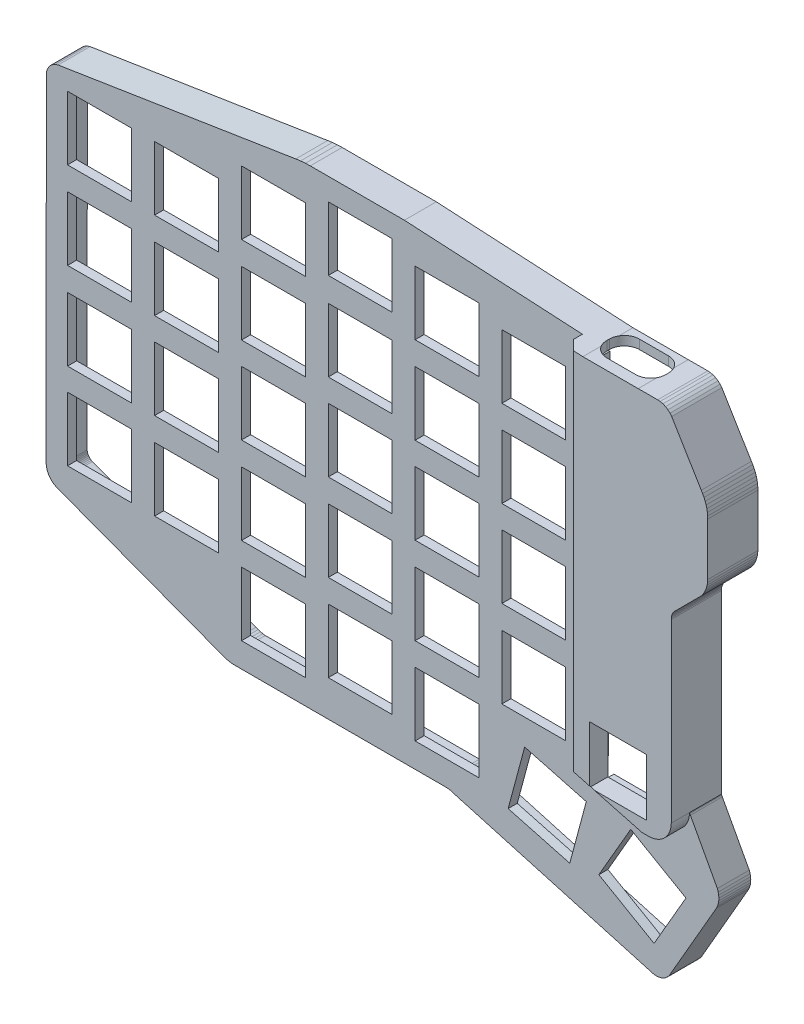
SolidWorks part; units mm, degrees
ref_plane "Plan de face" through (0, 0, 0) normal (0, 0, 1) x (1, 0, 0)
ref_plane "Plan de dessus" through (0, 0, 0) normal (0, 1, 0) x (1, 0, 0)
ref_plane "Plan de droite" through (0, 0, 0) normal (1, 0, 0) x (0, 0, -1)
ref_plane "Plan1" through (0, 0, 1.58) normal (0, 0, 1) x (1, 0, 0)
sketch "Esquisse1" plane through (0, 0, 1.58) normal (0, 0, 1) x (1, 0, 0)
  line L1 (-0.3866, -0.7297) -> (-0.4136, -74.5092)
  line L2 (-0.4136, -74.5092) -> (-0.3883, -74.773)
  line L3 (-0.3883, -74.773) -> (-0.3247, -75.0329)
  line L4 (-0.3247, -75.0329) -> (-0.2244, -75.2809)
  line L5 (-0.2244, -75.2809) -> (-0.0893, -75.5118)
  line L6 (-0.0893, -75.5118) -> (0.0777, -75.7208)
  line L7 (0.0777, -75.7208) -> (0.273, -75.9036)
  line L8 (0.273, -75.9036) -> (0.4926, -76.0563)
  line L9 (0.4926, -76.0563) -> (0.7301, -76.1748)
  line L10 (0.7301, -76.1748) -> (36.6435, -89.6923)
  line L11 (36.6435, -89.6923) -> (37.1238, -89.9016)
  line L12 (37.1238, -89.9016) -> (37.6283, -90.0674)
  line L13 (37.6283, -90.0674) -> (38.1462, -90.1852)
  line L14 (38.1462, -90.1852) -> (38.6746, -90.2544)
  line L15 (38.6746, -90.2544) -> (85.6753, -90.2544)
  line L16 (85.6753, -90.2544) -> (86.1765, -90.3127)
  line L17 (86.1765, -90.3127) -> (86.6747, -90.4058)
  line L18 (86.6747, -90.4058) -> (87.1654, -90.5328)
  line L19 (87.1654, -90.5328) -> (87.6517, -90.6952)
  line L20 (87.6517, -90.6952) -> (131.2378, -103.003)
  line L21 (131.2378, -103.003) -> (131.4732, -103.0269)
  line L22 (131.4732, -103.0269) -> (131.7087, -103.0123)
  line L23 (131.7087, -103.0123) -> (131.9388, -102.9598)
  line L24 (131.9388, -102.9598) -> (132.1573, -102.8708)
  line L25 (132.1573, -102.8708) -> (132.3586, -102.7476)
  line L26 (132.3586, -102.7476) -> (132.5372, -102.5934)
  line L27 (132.5372, -102.5934) -> (132.6889, -102.4119)
  line L28 (132.6889, -102.4119) -> (142.946, -84.5995)
  line L29 (142.946, -84.5995) -> (143.0686, -84.319)
  line L30 (143.0686, -84.319) -> (143.1566, -84.0252)
  line L31 (143.1566, -84.0252) -> (143.2087, -83.723)
  line L32 (143.2087, -83.723) -> (143.224, -83.4168)
  line L33 (143.224, -83.4168) -> (143.2024, -83.1109)
  line L34 (143.2024, -83.1109) -> (143.144, -82.8098)
  line L35 (143.144, -82.8098) -> (143.0489, -82.515)
  line L36 (143.0489, -82.515) -> (137.2436, -71.7551)
  line L37 (137.2436, -71.7551) -> (137.0784, -71.4776)
  line L38 (137.0784, -71.4776) -> (136.9471, -71.1909)
  line L39 (136.9471, -71.1909) -> (136.8472, -70.8917)
  line L40 (136.8472, -70.8917) -> (136.7811, -70.5888)
  line L41 (136.7811, -70.5888) -> (136.7811, -31.6019)
  line L42 (136.7811, -31.6019) -> (136.8019, -31.1498)
  line L43 (136.8019, -31.1498) -> (136.8638, -30.7037)
  line L44 (136.8638, -30.7037) -> (136.9664, -30.2653)
  line L45 (136.9664, -30.2653) -> (137.1088, -29.8381)
  line L46 (137.1088, -29.8381) -> (137.2898, -29.4258)
  line L47 (137.2898, -29.4258) -> (137.5079, -29.0319)
  line L48 (137.5079, -29.0319) -> (137.7585, -28.6636)
  line L49 (137.7585, -28.6636) -> (143.8574, -22.5647)
  line L50 (143.8574, -22.5647) -> (144.092, -22.2419)
  line L51 (144.092, -22.2419) -> (144.2935, -21.9012)
  line L52 (144.2935, -21.9012) -> (144.462, -21.543)
  line L53 (144.462, -21.543) -> (144.5961, -21.1706)
  line L54 (144.5961, -21.1706) -> (144.6945, -20.7872)
  line L55 (144.6945, -20.7872) -> (144.7564, -20.3962)
  line L56 (144.7564, -20.3962) -> (144.7811, -20.0027)
  line L57 (144.7811, -20.0027) -> (144.7811, -8.5985)
  line L58 (144.7811, -8.5985) -> (144.7708, -8.1037)
  line L59 (144.7708, -8.1037) -> (144.7223, -7.6084)
  line L60 (144.7223, -7.6084) -> (144.6361, -7.1183)
  line L61 (144.6361, -7.1183) -> (144.5126, -6.6362)
  line L62 (144.5126, -6.6362) -> (144.3526, -6.1649)
  line L63 (144.3526, -6.1649) -> (144.1571, -5.7072)
  line L64 (144.1571, -5.7072) -> (143.9271, -5.2659)
  line L65 (143.9271, -5.2659) -> (143.6664, -4.8473)
  line L66 (143.6664, -4.8473) -> (137.2313, 5.8197)
  line L67 (137.2313, 5.8197) -> (137.0475, 6.0477)
  line L68 (137.0475, 6.0477) -> (136.8282, 6.2436)
  line L69 (136.8282, 6.2436) -> (136.5799, 6.4014)
  line L70 (136.5799, 6.4014) -> (136.3093, 6.5168)
  line L71 (136.3093, 6.5168) -> (136.0236, 6.5867)
  line L72 (136.0236, 6.5867) -> (135.7344, 6.609)
  line L73 (135.7344, 6.609) -> (131.5173, 6.5929)
  line L74 (131.5173, 6.5929) -> (129.9175, 6.5929)
  line L75 (129.9175, 6.5929) -> (129.9175, 0.5929) construction
  line L76 (129.9175, 0.5929) -> (120.9175, 0.5929) construction
  line L77 (120.9175, 0.5929) -> (120.9175, 6.5929) construction
  line L78 (120.9175, 6.5929) -> (119.3202, 6.5929)
  line L79 (119.3202, 6.5929) -> (76.1593, 8.9456)
  line L80 (76.1593, 8.9456) -> (55.5795, 8.9456)
  line L81 (55.5795, 8.9456) -> (54.6048, 8.9137)
  line L82 (54.6048, 8.9137) -> (53.6322, 8.8315)
  line L83 (53.6322, 8.8315) -> (52.6666, 8.6994)
  line L84 (52.6666, 8.6994) -> (0.6588, 0.4982)
  line L85 (0.6588, 0.4982) -> (0.4232, 0.4271)
  line L86 (0.4232, 0.4271) -> (0.203, 0.3114)
  line L87 (0.203, 0.3114) -> (0.0087, 0.156)
  line L88 (0.0087, 0.156) -> (-0.1526, -0.0335)
  line L89 (-0.1526, -0.0335) -> (-0.275, -0.2501)
  line L90 (-0.275, -0.2501) -> (-0.3541, -0.486)
  line L91 (-0.3541, -0.486) -> (-0.3866, -0.7297)
  line L92 (119.3175, 6.4929) -> (76.1566, 8.8456)
  line L93 (76.1566, 8.8456) -> (55.5811, 8.8456)
  line L94 (55.5811, 8.8456) -> (54.6107, 8.8138)
  line L95 (54.6107, 8.8138) -> (53.6432, 8.732)
  line L96 (53.6432, 8.732) -> (52.6811, 8.6004)
  line L97 (52.6811, 8.6004) -> (0.6811, 0.4004)
  line L98 (0.6811, 0.4004) -> (0.4613, 0.3341)
  line L99 (0.4613, 0.3341) -> (0.258, 0.2273)
  line L100 (0.258, 0.2273) -> (0.0786, 0.0839)
  line L101 (0.0786, 0.0839) -> (-0.0703, -0.091)
  line L102 (-0.0703, -0.091) -> (-0.1833, -0.2909)
  line L103 (-0.1833, -0.2909) -> (-0.2563, -0.5087)
  line L104 (-0.2563, -0.5087) -> (-0.2866, -0.7363)
  line L105 (-0.2866, -0.7363) -> (-0.3136, -74.5044)
  line L106 (-0.3136, -74.5044) -> (-0.2895, -74.7563)
  line L107 (-0.2895, -74.7563) -> (-0.2293, -75.0021)
  line L108 (-0.2293, -75.0021) -> (-0.1344, -75.2366)
  line L109 (-0.1344, -75.2366) -> (-0.0066, -75.455)
  line L110 (-0.0066, -75.455) -> (0.1513, -75.6527)
  line L111 (0.1513, -75.6527) -> (0.336, -75.8256)
  line L112 (0.336, -75.8256) -> (0.5438, -75.9701)
  line L113 (0.5438, -75.9701) -> (0.7702, -76.0831)
  line L114 (0.7702, -76.0831) -> (36.6811, -89.5996)
  line L115 (36.6811, -89.5996) -> (37.1594, -89.808)
  line L116 (37.1594, -89.808) -> (37.6551, -89.9709)
  line L117 (37.6551, -89.9709) -> (38.1638, -90.0867)
  line L118 (38.1638, -90.0867) -> (38.6811, -90.1544)
  line L119 (38.6811, -90.1544) -> (85.6811, -90.1544)
  line L120 (85.6811, -90.1544) -> (86.1915, -90.2138)
  line L121 (86.1915, -90.2138) -> (86.6965, -90.3081)
  line L122 (86.6965, -90.3081) -> (87.1938, -90.4369)
  line L123 (87.1938, -90.4369) -> (87.6811, -90.5996)
  line L124 (87.6811, -90.5996) -> (131.2566, -102.9044)
  line L125 (131.2566, -102.9044) -> (131.4752, -102.9265)
  line L126 (131.4752, -102.9265) -> (131.6944, -102.913)
  line L127 (131.6944, -102.913) -> (131.9086, -102.8641)
  line L128 (131.9086, -102.8641) -> (132.1121, -102.7812)
  line L129 (132.1121, -102.7812) -> (132.2994, -102.6665)
  line L130 (132.2994, -102.6665) -> (132.4657, -102.523)
  line L131 (132.4657, -102.523) -> (132.6066, -102.3544)
  line L132 (132.6066, -102.3544) -> (142.8566, -84.5544)
  line L133 (142.8566, -84.5544) -> (142.9745, -84.2845)
  line L134 (142.9745, -84.2845) -> (143.0591, -84.0023)
  line L135 (143.0591, -84.0023) -> (143.1091, -83.712)
  line L136 (143.1091, -83.712) -> (143.1238, -83.4178)
  line L137 (143.1238, -83.4178) -> (143.103, -83.124)
  line L138 (143.103, -83.124) -> (143.047, -82.8348)
  line L139 (143.047, -82.8348) -> (142.9566, -82.5544)
  line L140 (142.9566, -82.5544) -> (137.1566, -71.8044)
  line L141 (137.1566, -71.8044) -> (136.9898, -71.5241)
  line L142 (136.9898, -71.5241) -> (136.8539, -71.2276)
  line L143 (136.8539, -71.2276) -> (136.7507, -70.9182)
  line L144 (136.7507, -70.9182) -> (136.6811, -70.5996)
  line L145 (136.6811, -70.5996) -> (136.6811, -31.5996)
  line L146 (136.6811, -31.5996) -> (136.7023, -31.1406)
  line L147 (136.7023, -31.1406) -> (136.7654, -30.6854)
  line L148 (136.7654, -30.6854) -> (136.8701, -30.238)
  line L149 (136.8701, -30.238) -> (137.0154, -29.8021)
  line L150 (137.0154, -29.8021) -> (137.2001, -29.3814)
  line L151 (137.2001, -29.3814) -> (137.4226, -28.9794)
  line L152 (137.4226, -28.9794) -> (137.6811, -28.5996)
  line L153 (137.6811, -28.5996) -> (143.7811, -22.4996)
  line L154 (143.7811, -22.4996) -> (144.0083, -22.187)
  line L155 (144.0083, -22.187) -> (144.205, -21.8544)
  line L156 (144.205, -21.8544) -> (144.3695, -21.5047)
  line L157 (144.3695, -21.5047) -> (144.5004, -21.1412)
  line L158 (144.5004, -21.1412) -> (144.5965, -20.7669)
  line L159 (144.5965, -20.7669) -> (144.6569, -20.3852)
  line L160 (144.6569, -20.3852) -> (144.6811, -19.9996)
  line L161 (144.6811, -19.9996) -> (144.6811, -8.5996)
  line L162 (144.6811, -8.5996) -> (144.6709, -8.1097)
  line L163 (144.6709, -8.1097) -> (144.6231, -7.622)
  line L164 (144.6231, -7.622) -> (144.5383, -7.1394)
  line L165 (144.5383, -7.1394) -> (144.4167, -6.6647)
  line L166 (144.4167, -6.6647) -> (144.2592, -6.2007)
  line L167 (144.2592, -6.2007) -> (144.0666, -5.7501)
  line L168 (144.0666, -5.7501) -> (143.8402, -5.3155)
  line L169 (143.8402, -5.3155) -> (143.5811, -4.8996)
  line L170 (143.5811, -4.8996) -> (137.1492, 5.7623)
  line L171 (137.1492, 5.7623) -> (136.9748, 5.9785)
  line L172 (136.9748, 5.9785) -> (136.7676, 6.1636)
  line L173 (136.7676, 6.1636) -> (136.5332, 6.3126)
  line L174 (136.5332, 6.3126) -> (136.2776, 6.4216)
  line L175 (136.2776, 6.4216) -> (136.0078, 6.4876)
  line L176 (136.0078, 6.4876) -> (135.7308, 6.509)
  line L177 (135.7308, 6.509) -> (131.5175, 6.4929)
  line L178 (131.5175, 6.4929) -> (130.0175, 6.4929)
  line L179 (130.0175, 6.4929) -> (130.0175, 0.4929)
  line L180 (130.0175, 0.4929) -> (120.8175, 0.4929)
  line L181 (120.8175, 0.4929) -> (120.8175, 6.4929)
  line L182 (120.8175, 6.4929) -> (119.3175, 6.4929)
  line L183 (119.3175, 6.4929) -> (76.1566, 8.8456) construction
  line L184 (76.1566, 8.8456) -> (55.5811, 8.8456) construction
  line L185 (55.5811, 8.8456) -> (54.6107, 8.8138) construction
  line L186 (54.6107, 8.8138) -> (53.6432, 8.732) construction
  line L187 (53.6432, 8.732) -> (52.6811, 8.6004) construction
  line L188 (52.6811, 8.6004) -> (0.6811, 0.4004) construction
  line L189 (0.6811, 0.4004) -> (0.4613, 0.3341) construction
  line L190 (0.4613, 0.3341) -> (0.258, 0.2273) construction
  line L191 (0.258, 0.2273) -> (0.0786, 0.0839) construction
  line L192 (0.0786, 0.0839) -> (-0.0703, -0.091) construction
  line L193 (-0.0703, -0.091) -> (-0.1833, -0.2909) construction
  line L194 (-0.1833, -0.2909) -> (-0.2563, -0.5087) construction
  line L195 (-0.2563, -0.5087) -> (-0.2866, -0.7363) construction
  line L196 (-0.2866, -0.7363) -> (-0.3136, -74.5044) construction
  line L197 (-0.3136, -74.5044) -> (-0.2895, -74.7563) construction
  line L198 (-0.2895, -74.7563) -> (-0.2293, -75.0021) construction
  line L199 (-0.2293, -75.0021) -> (-0.1344, -75.2366) construction
  line L200 (-0.1344, -75.2366) -> (-0.0066, -75.455) construction
  line L201 (-0.0066, -75.455) -> (0.1513, -75.6527) construction
  line L202 (0.1513, -75.6527) -> (0.336, -75.8256) construction
  line L203 (0.336, -75.8256) -> (0.5438, -75.9701) construction
  line L204 (0.5438, -75.9701) -> (0.7702, -76.0831) construction
  line L205 (0.7702, -76.0831) -> (36.6811, -89.5996) construction
  line L206 (36.6811, -89.5996) -> (37.1594, -89.808) construction
  line L207 (37.1594, -89.808) -> (37.6551, -89.9709) construction
  line L208 (37.6551, -89.9709) -> (38.1638, -90.0867) construction
  line L209 (38.1638, -90.0867) -> (38.6811, -90.1544) construction
  line L210 (38.6811, -90.1544) -> (85.6811, -90.1544) construction
  line L211 (85.6811, -90.1544) -> (86.1915, -90.2138) construction
  line L212 (86.1915, -90.2138) -> (86.6965, -90.3081) construction
  line L213 (86.6965, -90.3081) -> (87.1938, -90.4369) construction
  line L214 (87.1938, -90.4369) -> (87.6811, -90.5996) construction
  line L215 (87.6811, -90.5996) -> (131.2566, -102.9044) construction
  line L216 (131.2566, -102.9044) -> (131.4752, -102.9265) construction
  line L217 (131.4752, -102.9265) -> (131.6944, -102.913) construction
  line L218 (131.6944, -102.913) -> (131.9086, -102.8641) construction
  line L219 (131.9086, -102.8641) -> (132.1121, -102.7812) construction
  line L220 (132.1121, -102.7812) -> (132.2994, -102.6665) construction
  line L221 (132.2994, -102.6665) -> (132.4657, -102.523) construction
  line L222 (132.4657, -102.523) -> (132.6066, -102.3544) construction
  line L223 (132.6066, -102.3544) -> (142.8566, -84.5544) construction
  line L224 (142.8566, -84.5544) -> (142.9745, -84.2845) construction
  line L225 (142.9745, -84.2845) -> (143.0591, -84.0023) construction
  line L226 (143.0591, -84.0023) -> (143.1091, -83.712) construction
  line L227 (143.1091, -83.712) -> (143.1238, -83.4178) construction
  line L228 (143.1238, -83.4178) -> (143.103, -83.124) construction
  line L229 (143.103, -83.124) -> (143.047, -82.8348) construction
  line L230 (143.047, -82.8348) -> (142.9566, -82.5544) construction
  line L231 (142.9566, -82.5544) -> (137.1566, -71.8044) construction
  line L232 (137.1566, -71.8044) -> (136.9898, -71.5241) construction
  line L233 (136.9898, -71.5241) -> (136.8539, -71.2276) construction
  line L234 (136.8539, -71.2276) -> (136.7507, -70.9182) construction
  line L235 (136.7507, -70.9182) -> (136.6811, -70.5996) construction
  line L236 (136.6811, -70.5996) -> (136.6811, -31.5996) construction
  line L237 (136.6811, -31.5996) -> (136.7023, -31.1406) construction
  line L238 (136.7023, -31.1406) -> (136.7654, -30.6854) construction
  line L239 (136.7654, -30.6854) -> (136.8701, -30.238) construction
  line L240 (136.8701, -30.238) -> (137.0154, -29.8021) construction
  line L241 (137.0154, -29.8021) -> (137.2001, -29.3814) construction
  line L242 (137.2001, -29.3814) -> (137.4226, -28.9794) construction
  line L243 (137.4226, -28.9794) -> (137.6811, -28.5996) construction
  line L244 (137.6811, -28.5996) -> (143.7811, -22.4996) construction
  line L245 (143.7811, -22.4996) -> (144.0083, -22.187) construction
  line L246 (144.0083, -22.187) -> (144.205, -21.8544) construction
  line L247 (144.205, -21.8544) -> (144.3695, -21.5047) construction
  line L248 (144.3695, -21.5047) -> (144.5004, -21.1412) construction
  line L249 (144.5004, -21.1412) -> (144.5965, -20.7669) construction
  line L250 (144.5965, -20.7669) -> (144.6569, -20.3852) construction
  line L251 (144.6569, -20.3852) -> (144.6811, -19.9996) construction
  line L252 (144.6811, -19.9996) -> (144.6811, -8.5996) construction
  line L253 (144.6811, -8.5996) -> (144.6709, -8.1097) construction
  line L254 (144.6709, -8.1097) -> (144.6231, -7.622) construction
  line L255 (144.6231, -7.622) -> (144.5383, -7.1394) construction
  line L256 (144.5383, -7.1394) -> (144.4167, -6.6647) construction
  line L257 (144.4167, -6.6647) -> (144.2592, -6.2007) construction
  line L258 (144.2592, -6.2007) -> (144.0666, -5.7501) construction
  line L259 (144.0666, -5.7501) -> (143.8402, -5.3155) construction
  line L260 (143.8402, -5.3155) -> (143.5811, -4.8996) construction
  line L261 (143.5811, -4.8996) -> (137.1492, 5.7623) construction
  line L262 (137.1492, 5.7623) -> (136.9748, 5.9785) construction
  line L263 (136.9748, 5.9785) -> (136.7676, 6.1636) construction
  line L264 (136.7676, 6.1636) -> (136.5332, 6.3126) construction
  line L265 (136.5332, 6.3126) -> (136.2776, 6.4216) construction
  line L266 (136.2776, 6.4216) -> (136.0078, 6.4876) construction
  line L267 (136.0078, 6.4876) -> (135.7308, 6.509) construction
  line L268 (135.7308, 6.509) -> (131.5175, 6.4929) construction
  line L269 (131.5175, 6.4929) -> (130.0175, 6.4929) construction
  line L270 (130.0175, 6.4929) -> (130.0175, 0.4929) construction
  line L271 (130.0175, 0.4929) -> (120.8175, 0.4929) construction
  line L272 (120.8175, 0.4929) -> (120.8175, 6.4929) construction
  line L273 (120.8175, 6.4929) -> (119.3175, 6.4929) construction
  line L275 (120.9175, 6.5929) -> (129.9175, 6.5929)
  line L276 (-0.0707, -78.0104) -> (35.8912, -91.5461)
  line L277 (35.8912, -91.5461) -> (36.4105, -91.7724)
  line L278 (36.4105, -91.7724) -> (37.0931, -91.9967)
  line L279 (37.0931, -91.9967) -> (37.7937, -92.1562)
  line L280 (37.7937, -92.1562) -> (38.5443, -92.2544)
  line L281 (38.5443, -92.2544) -> (85.5594, -92.2544)
  line L282 (85.5594, -92.2544) -> (85.877, -92.2914)
  line L283 (85.877, -92.2914) -> (86.24, -92.3591)
  line L284 (86.24, -92.3591) -> (86.5974, -92.4517)
  line L285 (86.5974, -92.4517) -> (87.063, -92.6071)
  line L286 (87.063, -92.6071) -> (130.8625, -104.9753)
  line L287 (130.8625, -104.9753) -> (131.4339, -105.0331)
  line L288 (131.4339, -105.0331) -> (131.9947, -104.9984)
  line L289 (131.9947, -104.9984) -> (132.5425, -104.8735)
  line L290 (132.5425, -104.8735) -> (133.0628, -104.6615)
  line L291 (133.0628, -104.6615) -> (133.542, -104.3681)
  line L292 (133.542, -104.3681) -> (133.9674, -104.0009)
  line L293 (133.9674, -104.0009) -> (134.3352, -103.5608)
  line L294 (134.3352, -103.5608) -> (144.7344, -85.5017)
  line L295 (144.7344, -85.5017) -> (144.9496, -85.009)
  line L296 (144.9496, -85.009) -> (145.1071, -84.4839)
  line L297 (145.1071, -84.4839) -> (145.2002, -83.9436)
  line L298 (145.2002, -83.9436) -> (145.2276, -83.396)
  line L299 (145.2276, -83.396) -> (145.1888, -82.8491)
  line L300 (145.1888, -82.8491) -> (145.0845, -82.3109)
  line L301 (145.0845, -82.3109) -> (144.8961, -81.7267)
  line L302 (144.8961, -81.7267) -> (138.9837, -70.7683)
  line L303 (138.9837, -70.7683) -> (138.852, -70.547)
  line L304 (138.852, -70.547) -> (138.8102, -70.4557)
  line L305 (138.8102, -70.4557) -> (138.7811, -70.3687)
  line L306 (138.7811, -70.3687) -> (138.7811, -70.3687)
  line L307 (138.7811, -70.3687) -> (138.7811, -31.6478)
  line L308 (138.7811, -31.6478) -> (138.7956, -31.3335)
  line L309 (138.7956, -31.3335) -> (138.8322, -31.0698)
  line L310 (138.8322, -31.0698) -> (138.8929, -30.8105)
  line L311 (138.8929, -30.8105) -> (138.9771, -30.5579)
  line L312 (138.9771, -30.5579) -> (139.0841, -30.314)
  line L313 (139.0841, -30.314) -> (139.2131, -30.081)
  line L314 (139.2131, -30.081) -> (139.306, -29.9446)
  line L315 (139.306, -29.9446) -> (145.3829, -23.8677)
  line L316 (145.3829, -23.8677) -> (145.7654, -23.3413)
  line L317 (145.7654, -23.3413) -> (146.063, -22.8381)
  line L318 (146.063, -22.8381) -> (146.3118, -22.3092)
  line L319 (146.3118, -22.3092) -> (146.5098, -21.7593)
  line L320 (146.5098, -21.7593) -> (146.6552, -21.1931)
  line L321 (146.6552, -21.1931) -> (146.7466, -20.6158)
  line L322 (146.7466, -20.6158) -> (146.7811, -20.0655)
  line L323 (146.7811, -20.0655) -> (146.7811, -8.5775)
  line L324 (146.7811, -8.5775) -> (146.7687, -7.9852)
  line L325 (146.7687, -7.9852) -> (146.7053, -7.3374)
  line L326 (146.7053, -7.3374) -> (146.5926, -6.6963)
  line L327 (146.5926, -6.6963) -> (146.4311, -6.0658)
  line L328 (146.4311, -6.0658) -> (146.2219, -5.4494)
  line L329 (146.2219, -5.4494) -> (145.9661, -4.8509)
  line L330 (145.9661, -4.8509) -> (145.6653, -4.2737)
  line L331 (145.6653, -4.2737) -> (145.3716, -3.8021)
  line L332 (145.3716, -3.8021) -> (138.8736, 6.9693)
  line L333 (138.8736, 6.9693) -> (138.5019, 7.4303)
  line L334 (138.5019, 7.4303) -> (138.0388, 7.844)
  line L335 (138.0388, 7.844) -> (137.5147, 8.177)
  line L336 (137.5147, 8.177) -> (136.9435, 8.4206)
  line L337 (136.9435, 8.4206) -> (136.3403, 8.5682)
  line L338 (136.3403, 8.5682) -> (135.8076, 8.6093)
  line L339 (135.8076, 8.6093) -> (131.5135, 8.5929)
  line L340 (131.5135, 8.5929) -> (129.9175, 8.5929)
  line L341 (120.9175, 8.5929) -> (129.9175, 8.5929)
  line L342 (120.9175, 8.5929) -> (119.3747, 8.5929)
  line L343 (119.3747, 8.5929) -> (76.2138, 10.9456)
  line L344 (76.2138, 10.9456) -> (55.5468, 10.9456)
  line L345 (55.5468, 10.9456) -> (54.4878, 10.9109)
  line L346 (54.4878, 10.9109) -> (53.4123, 10.82)
  line L347 (53.4123, 10.82) -> (52.3753, 10.6782)
  line L348 (52.3753, 10.6782) -> (0.2123, 2.4525)
  line L349 (0.2123, 2.4525) -> (-0.3374, 2.2867)
  line L350 (-0.3374, 2.2867) -> (-0.8967, 1.9929)
  line L351 (-0.8967, 1.9929) -> (-1.3901, 1.5983)
  line L352 (-1.3901, 1.5983) -> (-1.7996, 1.1172)
  line L353 (-1.7996, 1.1172) -> (-2.1104, 0.5672)
  line L354 (-2.1104, 0.5672) -> (-2.3113, -0.0319)
  line L355 (-2.3113, -0.0319) -> (-2.3865, -0.5966)
  line L356 (-2.3865, -0.5966) -> (-2.4136, -74.6043)
  line L357 (-2.4136, -74.6043) -> (-2.3654, -75.1078)
  line L358 (-2.3654, -75.1078) -> (-2.233, -75.6491)
  line L359 (-2.233, -75.6491) -> (-2.0238, -76.1656)
  line L360 (-2.0238, -76.1656) -> (-1.7425, -76.6467)
  line L361 (-1.7425, -76.6467) -> (-1.3947, -77.0821)
  line L362 (-1.3947, -77.0821) -> (-0.9878, -77.4629)
  line L363 (-0.9878, -77.4629) -> (-0.5301, -77.7812)
  line L364 (-0.5301, -77.7812) -> (-0.0707, -78.0104)
  dimension "D1" = 0
  dimension "D2" = 0.1
  dimension "D3" = 2
extrude "Contour" add sketch "Esquisse1" against normal blind 5 and the other way blind 2
sketch "Esquisse2" plane through (0, 0, 1.58) normal (0, 0, 1) x (1, 0, 0)
  line L0 (16.1811, -1.5996) -> (16.1811, -15.3996) construction
  line L1 (21.4811, -39.6996) -> (35.2811, -39.6996) construction
  line L3 (16.1811, -59.7996) -> (16.1811, -60.5496) construction
  line L4 (21.4811, -72.6044) -> (21.4811, -58.8044) construction
  line L5 (21.4811, -3.3496) -> (21.4811, -2.5996) construction
  line L6 (35.3066, -1.5996) -> (35.3066, -15.3996) construction
  line L7 (40.5566, 3.3004) -> (40.5566, -10.4996) construction
  line L8 (54.3566, -86.7544) -> (54.3566, -72.9544) construction
  line L9 (34.2811, -39.6996) -> (22.4811, -39.6996) construction
  line L10 (21.4811, -58.8044) -> (35.3066, -58.8044) construction
  line L11 (59.6066, 6.0004) -> (59.6066, -7.7996) construction
  line L12 (73.4066, -84.2544) -> (73.4066, -70.4544) construction
  line L13 (78.6566, 3.3004) -> (78.6566, -10.4996) construction
  line L14 (92.4566, -86.7544) -> (92.4566, -72.9544) construction
  line L15 (3.3811, -58.7996) -> (15.1811, -58.7996) construction
  line L16 (34.3066, -58.8044) -> (22.5066, -58.8044) construction
  line L17 (97.7066, 0.7504) -> (97.7066, -13.0496) construction
  line L18 (35.3066, -72.6044) -> (21.4811, -72.6044) construction
  line L19 (111.5066, 0.7504) -> (111.5066, -13.0496) construction
  line L20 (15.1811, -53.6496) -> (3.3811, -53.6496) construction
  line L21 (40.5566, -66.7044) -> (40.5566, -65.9544) construction
  line L22 (35.3066, -70.8544) -> (35.3066, -71.6044) construction
  line L23 (54.3566, -85.0044) -> (54.3566, -85.7544) construction
  line L24 (59.6066, -83.2544) -> (59.6066, -82.5044) construction
  line L25 (73.4066, -82.5044) -> (73.4066, -83.2544) construction
  line L26 (78.6566, -85.7544) -> (78.6566, -85.0044) construction
  line L27 (92.4566, -85.0044) -> (92.4566, -85.7544) construction
  line L28 (97.7066, -69.2044) -> (97.7066, -68.4544) construction
  line L29 (111.5066, -57.4044) -> (111.5066, -58.1544) construction
  line L30 (102.6775, -76.1037) -> (99.1058, -89.4335) construction
  line L31 (99.3647, -88.4675) -> (99.5588, -87.7431) construction
  line L32 (116.0073, -79.6754) -> (112.4356, -93.0052) construction
  line L33 (112.8886, -91.3148) -> (112.6944, -92.0392) construction
  line L34 (119.021, -92.08) -> (130.9722, -98.98) construction
  line L35 (120.5366, -92.955) -> (119.887, -92.58) construction
  line L36 (125.921, -80.1288) -> (137.8722, -87.0288) construction
  line L37 (126.787, -80.6288) -> (127.4366, -81.0038) construction
  line L38 (2.3811, -1.5996) -> (2.3811, -15.3996) construction
  line L39 (2.3811, -71.5996) -> (2.3811, -70.8496) construction
  line L40 (22.5066, -72.6044) -> (34.3066, -72.6044) construction
  line L41 (3.3811, -39.8496) -> (15.1811, -39.8496) construction
  line L42 (21.4811, -53.4996) -> (35.2811, -53.4996) construction
  line L43 (22.4811, -53.4996) -> (34.2811, -53.4996) construction
  line L44 (2.3811, -72.5996) -> (16.1811, -72.5996) construction
  line L45 (35.2811, -39.6996) -> (35.2811, -53.4996) construction
  line L46 (15.2566, -34.5044) -> (3.4566, -34.5044) construction
  line L47 (15.1811, -72.5996) -> (3.3811, -72.5996) construction
  line L48 (2.3811, -58.7996) -> (16.1811, -58.7996) construction
  line L49 (15.1811, -15.3996) -> (3.3811, -15.3996) construction
  line L50 (2.3811, -53.6496) -> (16.1811, -53.6496) construction
  line L51 (2.3811, -39.8496) -> (16.1811, -39.8496) construction
  line L52 (3.4566, -20.7044) -> (15.2566, -20.7044) construction
  line L53 (35.3066, -34.5044) -> (21.4811, -34.5044) construction
  line L54 (2.3811, -20.7044) -> (16.1811, -20.7044) construction
  line L55 (2.3811, -15.3996) -> (16.1811, -15.3996) construction
  line L56 (2.3811, -1.5996) -> (16.1811, -1.5996) construction
  line L57 (40.5566, 3.3004) -> (54.3566, 3.3004) construction
  line L58 (59.6066, 6.0004) -> (73.4066, 6.0004) construction
  line L59 (40.5566, -10.4996) -> (54.3566, -10.4996) construction
  line L60 (92.4566, -15.7996) -> (78.6566, -15.7996) construction
  line L61 (40.5566, -29.5996) -> (54.3566, -29.5996) construction
  line L62 (92.4566, -34.7996) -> (78.6566, -34.7996) construction
  line L63 (40.5566, -48.5996) -> (54.3566, -48.5996) construction
  line L64 (2.3811, -58.7996) -> (2.3811, -72.5996) construction
  line L67 (16.1811, -58.7996) -> (16.1811, -72.5996) construction
  line L68 (35.2811, -52.4996) -> (35.2811, -40.6996) construction
  line L69 (21.4811, -53.4996) -> (21.4811, -39.6996) construction
  line L70 (35.3066, -58.8044) -> (35.3066, -72.6044) construction
  line L72 (21.4811, -34.5044) -> (21.4811, -20.7044) construction
  line L73 (16.1811, -39.8496) -> (16.1811, -53.6496) construction
  line L74 (2.3811, -39.8496) -> (2.3811, -53.6496) construction
  line L75 (35.3066, -39.8496) -> (35.3074, -39.8496)
  line L76 (16.1811, -34.5044) -> (2.3811, -34.5044) construction
  line L77 (2.3811, -20.7044) -> (2.3811, -34.5044) construction
  line L78 (16.1811, -20.7044) -> (16.1811, -34.5044) construction
  line L79 (21.4811, -15.3996) -> (21.4811, -1.5996) construction
  line L80 (35.3066, -20.7044) -> (35.3066, -34.5044) construction
  line L81 (21.4811, -15.3996) -> (35.3066, -15.3996) construction
  line L82 (21.4811, -20.7044) -> (35.3066, -20.7044) construction
  line L83 (21.4811, -1.5996) -> (35.3066, -1.5996) construction
  line L84 (41.4811, 3.3004) -> (53.2811, 3.3004) construction
  line L85 (60.5811, 6.0004) -> (72.3811, 6.0004) construction
  line L86 (78.6566, 3.3004) -> (92.4566, 3.3004) construction
  line L87 (53.2811, -10.4996) -> (41.4811, -10.4996) construction
  line L88 (41.4811, -15.7996) -> (53.2811, -15.7996) construction
  line L89 (53.2811, -29.5996) -> (41.4811, -29.5996) construction
  line L90 (41.4811, -34.7996) -> (53.2811, -34.7996) construction
  line L91 (53.2811, -48.5996) -> (41.4811, -48.5996) construction
  line L92 (40.5566, -53.9044) -> (54.3566, -53.9044) construction
  line L93 (92.4566, -67.7044) -> (78.6566, -67.7044) construction
  line L94 (54.3566, -15.7996) -> (40.5566, -15.7996) construction
  line L95 (78.6566, -10.4996) -> (92.4566, -10.4996) construction
  line L96 (78.6566, -29.5996) -> (92.4566, -29.5996) construction
  line L97 (54.3566, -34.7996) -> (40.5566, -34.7996) construction
  line L98 (78.6566, -48.5996) -> (92.4566, -48.5996) construction
  line L99 (54.3566, -29.5996) -> (54.3566, -15.7996) construction
  line L100 (40.5566, -34.7996) -> (40.5566, -48.5996) construction
  line L101 (54.3566, -10.4996) -> (54.3566, 3.3004) construction
  line L102 (40.5566, -15.7996) -> (40.5566, -29.5996) construction
  line L103 (54.3566, -48.5996) -> (54.3566, -34.7996) construction
  line L104 (40.5566, -53.9044) -> (40.5566, -67.7044) construction
  line L105 (41.5566, -53.9044) -> (53.3566, -53.9044) construction
  line L106 (53.3566, -67.7044) -> (41.5566, -67.7044) construction
  line L107 (78.6566, -53.9044) -> (92.4566, -53.9044) construction
  line L108 (40.5566, -72.9544) -> (54.3566, -72.9544) construction
  line L109 (40.5566, -86.7544) -> (54.3566, -86.7544) construction
  line L110 (53.3566, -86.7544) -> (41.5566, -86.7544) construction
  line L111 (41.5566, -72.9544) -> (53.3566, -72.9544) construction
  line L112 (40.5566, -72.9544) -> (40.5566, -86.7544) construction
  line L113 (54.3566, -67.7044) -> (54.3566, -53.9044) construction
  line L114 (54.3566, -67.7044) -> (40.5566, -67.7044) construction
  line L115 (78.6566, -72.9544) -> (92.4566, -72.9544) construction
  line L116 (78.6566, -86.7544) -> (92.4566, -86.7544) construction
  line L117 (78.6566, -15.7996) -> (78.6566, -29.5996) construction
  line L118 (92.4566, -10.4996) -> (92.4566, 3.3004) construction
  line L119 (92.4566, -29.5996) -> (92.4566, -15.7996) construction
  line L120 (78.6566, -34.7996) -> (78.6566, -48.5996) construction
  line L121 (78.6566, -53.9044) -> (78.6566, -67.7044) construction
  line L122 (92.4566, -48.5996) -> (92.4566, -34.7996) construction
  line L123 (92.4566, -67.7044) -> (92.4566, -53.9044) construction
  line L124 (78.6566, -72.9544) -> (78.6566, -86.7544) construction
  line L125 (59.6066, -84.2544) -> (73.4066, -84.2544) construction
  line L126 (73.4066, -70.4544) -> (59.6066, -70.4544) construction
  line L127 (59.6066, -65.2044) -> (73.4066, -65.2044) construction
  line L128 (59.6066, -51.4044) -> (73.4066, -51.4044) construction
  line L129 (73.4066, -46.0996) -> (59.6066, -46.0996) construction
  line L130 (59.6066, -32.2996) -> (73.4066, -32.2996) construction
  line L131 (73.4066, -27.0996) -> (59.6066, -27.0996) construction
  line L132 (59.6066, -13.2996) -> (73.4066, -13.2996) construction
  line L133 (73.4066, -7.7996) -> (59.6066, -7.7996) construction
  line L134 (72.3811, -7.7996) -> (60.5811, -7.7996) construction
  line L135 (72.3811, -27.0996) -> (60.5811, -27.0996) construction
  line L136 (72.3811, -46.0996) -> (60.5811, -46.0996) construction
  line L137 (72.4066, -65.2044) -> (60.6066, -65.2044) construction
  line L138 (72.4066, -84.2544) -> (60.6066, -84.2544) construction
  line L139 (60.5811, -13.2996) -> (72.3811, -13.2996) construction
  line L140 (60.5811, -32.2996) -> (72.3811, -32.2996) construction
  line L141 (60.6066, -51.4044) -> (72.4066, -51.4044) construction
  line L142 (60.6066, -70.4544) -> (72.4066, -70.4544) construction
  line L143 (59.6066, -13.2996) -> (59.6066, -27.0996) construction
  line L144 (73.4066, -7.7996) -> (73.4066, 6.0004) construction
  line L145 (73.4066, -27.0996) -> (73.4066, -13.2996) construction
  line L146 (59.6066, -32.2996) -> (59.6066, -46.0996) construction
  line L147 (73.4066, -46.0996) -> (73.4066, -32.2996) construction
  line L148 (59.6066, -51.4044) -> (59.6066, -65.2044) construction
  line L149 (73.4066, -65.2044) -> (73.4066, -51.4044) construction
  line L150 (59.6066, -70.4544) -> (59.6066, -84.2544) construction
  line L151 (102.6775, -76.1037) -> (116.0073, -79.6754) construction
  line L152 (99.1058, -89.4335) -> (112.4356, -93.0052) construction
  line L153 (119.021, -92.08) -> (125.921, -80.1288) construction
  line L154 (137.8722, -87.0288) -> (130.9722, -98.98) construction
  line L155 (97.7066, -70.2044) -> (111.5066, -70.2044) construction
  line L156 (97.7066, -56.4044) -> (111.5066, -56.4044) construction
  line L157 (97.7066, -51.0996) -> (111.5066, -51.0996) construction
  line L158 (97.7066, -37.2996) -> (111.5066, -37.2996) construction
  line L159 (97.7066, -32.0996) -> (111.5066, -32.0996) construction
  line L160 (97.7066, -18.2996) -> (111.5066, -18.2996) construction
  line L161 (111.5066, -13.0496) -> (97.7066, -13.0496) construction
  line L162 (97.7066, 0.7504) -> (111.5066, 0.7504) construction
  line L163 (110.4811, 0.7504) -> (98.6811, 0.7504) construction
  line L164 (98.6811, -13.0496) -> (110.4811, -13.0496) construction
  line L165 (110.4811, -18.2996) -> (98.6811, -18.2996) construction
  line L166 (98.6811, -32.0996) -> (110.4811, -32.0996) construction
  line L167 (110.4811, -37.2996) -> (98.6811, -37.2996) construction
  line L168 (98.6811, -51.0996) -> (110.4811, -51.0996) construction
  line L169 (110.5066, -56.4044) -> (98.7066, -56.4044) construction
  line L170 (98.7066, -70.2044) -> (110.5066, -70.2044) construction
  line L171 (115.0414, -79.4166) -> (103.6435, -76.3625) construction
  line L172 (100.0718, -89.6923) -> (111.4697, -92.7463) construction
  line L173 (125.421, -80.9949) -> (119.521, -91.214) construction
  line L174 (131.4722, -98.114) -> (137.3722, -87.8949) construction
  line L175 (111.5066, -56.4044) -> (111.5066, -70.2044) construction
  line L176 (97.7066, -56.4044) -> (97.7066, -70.2044) construction
  line L177 (97.7066, -37.2996) -> (97.7066, -51.0996) construction
  line L178 (111.5066, -37.2996) -> (111.5066, -51.0996) construction
  line L179 (111.5066, -18.2996) -> (111.5066, -32.0996) construction
  line L180 (97.7066, -18.2996) -> (97.7066, -32.0996) construction
  line L184 (121.5561, -60.2496) -> (125.9561, -60.2496) construction
  line L185 (119.0561, -59.2496) -> (135.1561, -59.2496)
  line L186 (119.0561, -59.2496) -> (119.0561, -73.3496)
  line L187 (119.0561, -73.3496) -> (135.1561, -73.3496)
  line L188 (135.1561, -59.2496) -> (135.1561, -73.3496)
  line L190 (121.0561, -60.7496) -> (121.0561, -71.8496) construction
  line L191 (125.9561, -72.3496) -> (121.5561, -72.3496) construction
  line L192 (133.1561, -71.8496) -> (133.1561, -60.7496) construction
  line L193 (15.1811, -1.5996) -> (3.3811, -1.5996) construction
  line L194 (34.2811, -1.5996) -> (22.4811, -1.5996) construction
  line L195 (2.2811, -1.4996) -> (16.2811, -1.4996)
  line L196 (16.2811, -1.4996) -> (16.2811, -15.4996)
  line L197 (2.2811, -15.4996) -> (16.2811, -15.4996)
  line L198 (2.2811, -1.4996) -> (2.2811, -15.4996)
  line L199 (21.3811, -15.4996) -> (21.3811, -1.4996)
  line L200 (21.3811, -1.4996) -> (35.4066, -1.4996)
  line L201 (35.4066, -1.4996) -> (35.4066, -15.4996)
  line L202 (21.3811, -15.4996) -> (35.4066, -15.4996)
  line L203 (35.4066, -20.6044) -> (35.4066, -34.6044)
  line L204 (35.4066, -34.6044) -> (21.3811, -34.6044)
  line L205 (21.3811, -34.6044) -> (21.3811, -20.6044)
  line L206 (21.3811, -20.6044) -> (35.4066, -20.6044)
  line L207 (2.2811, -20.6044) -> (16.2811, -20.6044)
  line L208 (16.2811, -20.6044) -> (16.2811, -34.6044)
  line L209 (16.2811, -34.6044) -> (2.2811, -34.6044)
  line L210 (2.2811, -20.6044) -> (2.2811, -34.6044)
  line L211 (2.2811, -39.7496) -> (16.2811, -39.7496)
  line L212 (16.2811, -39.7496) -> (16.2811, -53.7496)
  line L213 (2.2811, -53.7496) -> (16.2811, -53.7496)
  line L214 (2.2811, -39.7496) -> (2.2811, -53.7496)
  line L215 (21.3811, -53.5996) -> (35.3811, -53.5996)
  line L216 (35.3811, -39.5996) -> (35.3811, -53.5996)
  line L217 (21.3811, -39.5996) -> (35.3811, -39.5996)
  line L218 (21.3811, -53.5996) -> (21.3811, -39.5996)
  line L219 (35.4066, -72.7044) -> (21.3811, -72.7044)
  line L220 (21.3811, -72.7044) -> (21.3811, -58.7044)
  line L221 (21.3811, -58.7044) -> (35.4066, -58.7044)
  line L222 (35.4066, -58.7044) -> (35.4066, -72.7044)
  line L223 (2.2811, -72.6996) -> (16.2811, -72.6996)
  line L224 (16.2811, -58.6996) -> (16.2811, -72.6996)
  line L225 (2.2811, -58.6996) -> (16.2811, -58.6996)
  line L226 (2.2811, -58.6996) -> (2.2811, -72.6996)
  line L227 (40.4566, -53.8044) -> (54.4566, -53.8044)
  line L228 (54.4566, -67.8044) -> (54.4566, -53.8044)
  line L229 (54.4566, -67.8044) -> (40.4566, -67.8044)
  line L230 (40.4566, -53.8044) -> (40.4566, -67.8044)
  line L231 (54.4566, -86.8544) -> (54.4566, -72.8544)
  line L232 (40.4566, -72.8544) -> (54.4566, -72.8544)
  line L233 (40.4566, -72.8544) -> (40.4566, -86.8544)
  line L234 (40.4566, -86.8544) -> (54.4566, -86.8544)
  line L235 (40.4566, -48.6996) -> (54.4566, -48.6996)
  line L236 (54.4566, -48.6996) -> (54.4566, -34.6996)
  line L237 (54.4566, -34.6996) -> (40.4566, -34.6996)
  line L238 (40.4566, -34.6996) -> (40.4566, -48.6996)
  line L239 (54.4566, -15.6996) -> (40.4566, -15.6996)
  line L240 (40.4566, -15.6996) -> (40.4566, -29.6996)
  line L241 (40.4566, -29.6996) -> (54.4566, -29.6996)
  line L242 (54.4566, -29.6996) -> (54.4566, -15.6996)
  line L243 (40.4566, -10.5996) -> (54.4566, -10.5996)
  line L244 (54.4566, -10.5996) -> (54.4566, 3.4004)
  line L245 (40.4566, 3.4004) -> (54.4566, 3.4004)
  line L246 (40.4566, 3.4004) -> (40.4566, -10.5996)
  line L247 (59.5066, 6.1004) -> (59.5066, -7.8996)
  line L248 (73.5066, -7.8996) -> (59.5066, -7.8996)
  line L249 (73.5066, -7.8996) -> (73.5066, 6.1004)
  line L250 (59.5066, 6.1004) -> (73.5066, 6.1004)
  line L251 (59.5066, -13.1996) -> (73.5066, -13.1996)
  line L252 (73.5066, -27.1996) -> (73.5066, -13.1996)
  line L253 (73.5066, -27.1996) -> (59.5066, -27.1996)
  line L254 (59.5066, -13.1996) -> (59.5066, -27.1996)
  line L255 (59.5066, -32.1996) -> (73.5066, -32.1996)
  line L256 (73.5066, -46.1996) -> (73.5066, -32.1996)
  line L257 (73.5066, -46.1996) -> (59.5066, -46.1996)
  line L258 (59.5066, -32.1996) -> (59.5066, -46.1996)
  line L259 (59.5066, -51.3044) -> (73.5066, -51.3044)
  line L260 (73.5066, -65.3044) -> (73.5066, -51.3044)
  line L261 (59.5066, -65.3044) -> (73.5066, -65.3044)
  line L262 (59.5066, -51.3044) -> (59.5066, -65.3044)
  line L263 (73.5066, -84.3544) -> (73.5066, -70.3544)
  line L264 (73.5066, -70.3544) -> (59.5066, -70.3544)
  line L265 (59.5066, -70.3544) -> (59.5066, -84.3544)
  line L266 (59.5066, -84.3544) -> (73.5066, -84.3544)
  line L267 (92.5566, -86.8544) -> (92.5566, -72.8544)
  line L268 (78.5566, -72.8544) -> (92.5566, -72.8544)
  line L269 (-0.3866, -0.7297) -> (-0.4136, -74.5092)
  line L270 (-0.3541, -0.486) -> (-0.3866, -0.7297)
  line L271 (-0.275, -0.2501) -> (-0.3541, -0.486)
  line L272 (-0.1526, -0.0335) -> (-0.275, -0.2501)
  line L273 (0.0087, 0.156) -> (-0.1526, -0.0335)
  line L274 (0.203, 0.3114) -> (0.0087, 0.156)
  line L275 (0.4232, 0.4271) -> (0.203, 0.3114)
  line L276 (0.6588, 0.4982) -> (0.4232, 0.4271)
  line L277 (52.6666, 8.6994) -> (0.6588, 0.4982)
  line L278 (53.6322, 8.8315) -> (52.6666, 8.6994)
  line L279 (54.6048, 8.9137) -> (53.6322, 8.8315)
  line L280 (55.5795, 8.9456) -> (54.6048, 8.9137)
  line L281 (76.1593, 8.9456) -> (55.5795, 8.9456)
  line L282 (119.3202, 6.5929) -> (76.1593, 8.9456)
  line L283 (131.5173, 6.5929) -> (119.3202, 6.5929)
  line L284 (135.7344, 6.609) -> (131.5173, 6.5929)
  line L285 (136.0236, 6.5867) -> (135.7344, 6.609)
  line L286 (136.3093, 6.5168) -> (136.0236, 6.5867)
  line L287 (136.5799, 6.4014) -> (136.3093, 6.5168)
  line L288 (136.8282, 6.2436) -> (136.5799, 6.4014)
  line L289 (137.0475, 6.0477) -> (136.8282, 6.2436)
  line L290 (137.2313, 5.8197) -> (137.0475, 6.0477)
  line L291 (143.6664, -4.8473) -> (137.2313, 5.8197)
  line L292 (143.9271, -5.2659) -> (143.6664, -4.8473)
  line L293 (144.1571, -5.7072) -> (143.9271, -5.2659)
  line L294 (144.3526, -6.1649) -> (144.1571, -5.7072)
  line L295 (144.5126, -6.6362) -> (144.3526, -6.1649)
  line L296 (144.6361, -7.1183) -> (144.5126, -6.6362)
  line L297 (144.7223, -7.6084) -> (144.6361, -7.1183)
  line L298 (144.7708, -8.1037) -> (144.7223, -7.6084)
  line L299 (144.7811, -8.5985) -> (144.7708, -8.1037)
  line L300 (144.7811, -20.0027) -> (144.7811, -8.5985)
  line L301 (144.7564, -20.3962) -> (144.7811, -20.0027)
  line L302 (144.6945, -20.7872) -> (144.7564, -20.3962)
  line L303 (144.5961, -21.1706) -> (144.6945, -20.7872)
  line L304 (144.462, -21.543) -> (144.5961, -21.1706)
  line L305 (144.2935, -21.9012) -> (144.462, -21.543)
  line L306 (144.092, -22.2419) -> (144.2935, -21.9012)
  line L307 (143.8574, -22.5647) -> (144.092, -22.2419)
  line L308 (137.7585, -28.6636) -> (143.8574, -22.5647)
  line L309 (137.5079, -29.0319) -> (137.7585, -28.6636)
  line L310 (137.2898, -29.4258) -> (137.5079, -29.0319)
  line L311 (137.1088, -29.8381) -> (137.2898, -29.4258)
  line L312 (136.9664, -30.2653) -> (137.1088, -29.8381)
  line L313 (136.8638, -30.7037) -> (136.9664, -30.2653)
  line L314 (136.8019, -31.1498) -> (136.8638, -30.7037)
  line L315 (136.7811, -31.6019) -> (136.8019, -31.1498)
  line L316 (136.7811, -70.5888) -> (136.7811, -31.6019)
  line L317 (136.8472, -70.8917) -> (136.7811, -70.5888)
  line L318 (136.9471, -71.1909) -> (136.8472, -70.8917)
  line L319 (137.0784, -71.4776) -> (136.9471, -71.1909)
  line L320 (137.2436, -71.7551) -> (137.0784, -71.4776)
  line L321 (143.0489, -82.515) -> (137.2436, -71.7551)
  line L322 (143.144, -82.8098) -> (143.0489, -82.515)
  line L323 (143.2024, -83.1109) -> (143.144, -82.8098)
  line L324 (143.224, -83.4168) -> (143.2024, -83.1109)
  line L325 (143.2087, -83.723) -> (143.224, -83.4168)
  line L326 (143.1566, -84.0252) -> (143.2087, -83.723)
  line L327 (143.0686, -84.319) -> (143.1566, -84.0252)
  line L328 (142.946, -84.5995) -> (143.0686, -84.319)
  line L329 (132.6889, -102.4119) -> (142.946, -84.5995)
  line L330 (132.5372, -102.5934) -> (132.6889, -102.4119)
  line L331 (132.3586, -102.7476) -> (132.5372, -102.5934)
  line L332 (132.1573, -102.8708) -> (132.3586, -102.7476)
  line L333 (131.9388, -102.9598) -> (132.1573, -102.8708)
  line L334 (131.7087, -103.0123) -> (131.9388, -102.9598)
  line L335 (131.4732, -103.0269) -> (131.7087, -103.0123)
  line L336 (131.2378, -103.003) -> (131.4732, -103.0269)
  line L337 (87.6517, -90.6952) -> (131.2378, -103.003)
  line L338 (87.1654, -90.5328) -> (87.6517, -90.6952)
  line L339 (86.6747, -90.4058) -> (87.1654, -90.5328)
  line L340 (86.1765, -90.3127) -> (86.6747, -90.4058)
  line L341 (85.6753, -90.2544) -> (86.1765, -90.3127)
  line L342 (38.6746, -90.2544) -> (85.6753, -90.2544)
  line L343 (38.1462, -90.1852) -> (38.6746, -90.2544)
  line L344 (37.6283, -90.0674) -> (38.1462, -90.1852)
  line L345 (37.1238, -89.9016) -> (37.6283, -90.0674)
  line L346 (36.6435, -89.6923) -> (37.1238, -89.9016)
  line L347 (0.7301, -76.1748) -> (36.6435, -89.6923)
  line L348 (0.4926, -76.0563) -> (0.7301, -76.1748)
  line L349 (0.273, -75.9036) -> (0.4926, -76.0563)
  line L350 (0.0777, -75.7208) -> (0.273, -75.9036)
  line L351 (-0.0893, -75.5118) -> (0.0777, -75.7208)
  line L352 (-0.2244, -75.2809) -> (-0.0893, -75.5118)
  line L353 (-0.3247, -75.0329) -> (-0.2244, -75.2809)
  line L354 (-0.3883, -74.773) -> (-0.3247, -75.0329)
  line L355 (-0.4136, -74.5092) -> (-0.3883, -74.773)
  line L356 (-0.3866, -0.7297) -> (-0.4136, -74.5092)
  line L357 (-0.3541, -0.486) -> (-0.3866, -0.7297)
  line L358 (-0.275, -0.2501) -> (-0.3541, -0.486)
  line L359 (-0.1526, -0.0335) -> (-0.275, -0.2501)
  line L360 (0.0087, 0.156) -> (-0.1526, -0.0335)
  line L361 (0.203, 0.3114) -> (0.0087, 0.156)
  line L362 (0.4232, 0.4271) -> (0.203, 0.3114)
  line L363 (0.6588, 0.4982) -> (0.4232, 0.4271)
  line L364 (52.6666, 8.6994) -> (0.6588, 0.4982)
  line L365 (53.6322, 8.8315) -> (52.6666, 8.6994)
  line L366 (54.6048, 8.9137) -> (53.6322, 8.8315)
  line L367 (55.5795, 8.9456) -> (54.6048, 8.9137)
  line L368 (76.1593, 8.9456) -> (55.5795, 8.9456)
  line L369 (119.3202, 6.5929) -> (76.1593, 8.9456)
  line L370 (131.5173, 6.5929) -> (119.3202, 6.5929)
  line L371 (135.7344, 6.609) -> (131.5173, 6.5929)
  line L372 (136.0236, 6.5867) -> (135.7344, 6.609)
  line L373 (136.3093, 6.5168) -> (136.0236, 6.5867)
  line L374 (136.5799, 6.4014) -> (136.3093, 6.5168)
  line L375 (136.8282, 6.2436) -> (136.5799, 6.4014)
  line L376 (137.0475, 6.0477) -> (136.8282, 6.2436)
  line L377 (137.2313, 5.8197) -> (137.0475, 6.0477)
  line L378 (143.6664, -4.8473) -> (137.2313, 5.8197)
  line L379 (143.9271, -5.2659) -> (143.6664, -4.8473)
  line L380 (144.1571, -5.7072) -> (143.9271, -5.2659)
  line L381 (144.3526, -6.1649) -> (144.1571, -5.7072)
  line L382 (144.5126, -6.6362) -> (144.3526, -6.1649)
  line L383 (144.6361, -7.1183) -> (144.5126, -6.6362)
  line L384 (144.7223, -7.6084) -> (144.6361, -7.1183)
  line L385 (144.7708, -8.1037) -> (144.7223, -7.6084)
  line L386 (144.7811, -8.5985) -> (144.7708, -8.1037)
  line L387 (144.7811, -20.0027) -> (144.7811, -8.5985)
  line L388 (144.7564, -20.3962) -> (144.7811, -20.0027)
  line L389 (144.6945, -20.7872) -> (144.7564, -20.3962)
  line L390 (144.5961, -21.1706) -> (144.6945, -20.7872)
  line L391 (144.462, -21.543) -> (144.5961, -21.1706)
  line L392 (144.2935, -21.9012) -> (144.462, -21.543)
  line L393 (144.092, -22.2419) -> (144.2935, -21.9012)
  line L394 (143.8574, -22.5647) -> (144.092, -22.2419)
  line L395 (137.7585, -28.6636) -> (143.8574, -22.5647)
  line L396 (137.5079, -29.0319) -> (137.7585, -28.6636)
  line L397 (137.2898, -29.4258) -> (137.5079, -29.0319)
  line L398 (137.1088, -29.8381) -> (137.2898, -29.4258)
  line L399 (136.9664, -30.2653) -> (137.1088, -29.8381)
  line L400 (136.8638, -30.7037) -> (136.9664, -30.2653)
  line L401 (136.8019, -31.1498) -> (136.8638, -30.7037)
  line L402 (136.7811, -31.6019) -> (136.8019, -31.1498)
  line L403 (136.7811, -70.5888) -> (136.7811, -31.6019)
  line L404 (136.8472, -70.8917) -> (136.7811, -70.5888)
  line L405 (136.9471, -71.1909) -> (136.8472, -70.8917)
  line L406 (137.0784, -71.4776) -> (136.9471, -71.1909)
  line L407 (137.2436, -71.7551) -> (137.0784, -71.4776)
  line L408 (143.0489, -82.515) -> (137.2436, -71.7551)
  line L409 (143.144, -82.8098) -> (143.0489, -82.515)
  line L410 (143.2024, -83.1109) -> (143.144, -82.8098)
  line L411 (143.224, -83.4168) -> (143.2024, -83.1109)
  line L412 (143.2087, -83.723) -> (143.224, -83.4168)
  line L413 (143.1566, -84.0252) -> (143.2087, -83.723)
  line L414 (143.0686, -84.319) -> (143.1566, -84.0252)
  line L415 (142.946, -84.5995) -> (143.0686, -84.319)
  line L416 (132.6889, -102.4119) -> (142.946, -84.5995)
  line L417 (132.5372, -102.5934) -> (132.6889, -102.4119)
  line L418 (132.3586, -102.7476) -> (132.5372, -102.5934)
  line L419 (132.1573, -102.8708) -> (132.3586, -102.7476)
  line L420 (131.9388, -102.9598) -> (132.1573, -102.8708)
  line L421 (131.7087, -103.0123) -> (131.9388, -102.9598)
  line L422 (131.4732, -103.0269) -> (131.7087, -103.0123)
  line L423 (131.2378, -103.003) -> (131.4732, -103.0269)
  line L424 (87.6517, -90.6952) -> (131.2378, -103.003)
  line L425 (87.1654, -90.5328) -> (87.6517, -90.6952)
  line L426 (86.6747, -90.4058) -> (87.1654, -90.5328)
  line L427 (86.1765, -90.3127) -> (86.6747, -90.4058)
  line L428 (85.6753, -90.2544) -> (86.1765, -90.3127)
  line L429 (38.6746, -90.2544) -> (85.6753, -90.2544)
  line L430 (38.1462, -90.1852) -> (38.6746, -90.2544)
  line L431 (37.6283, -90.0674) -> (38.1462, -90.1852)
  line L432 (37.1238, -89.9016) -> (37.6283, -90.0674)
  line L433 (36.6435, -89.6923) -> (37.1238, -89.9016)
  line L434 (0.7301, -76.1748) -> (36.6435, -89.6923)
  line L435 (0.4926, -76.0563) -> (0.7301, -76.1748)
  line L436 (0.273, -75.9036) -> (0.4926, -76.0563)
  line L437 (0.0777, -75.7208) -> (0.273, -75.9036)
  line L438 (-0.0893, -75.5118) -> (0.0777, -75.7208)
  line L439 (-0.2244, -75.2809) -> (-0.0893, -75.5118)
  line L440 (-0.3247, -75.0329) -> (-0.2244, -75.2809)
  line L441 (-0.3883, -74.773) -> (-0.3247, -75.0329)
  line L442 (-0.4136, -74.5092) -> (-0.3883, -74.773)
  line L443 (78.5566, -72.8544) -> (78.5566, -86.8544)
  line L444 (78.5566, -86.8544) -> (92.5566, -86.8544)
  line L445 (78.5566, -53.8044) -> (92.5566, -53.8044)
  line L446 (92.5566, -67.8044) -> (92.5566, -53.8044)
  line L447 (92.5566, -67.8044) -> (78.5566, -67.8044)
  line L448 (78.5566, -53.8044) -> (78.5566, -67.8044)
  line L449 (92.5566, -34.6996) -> (78.5566, -34.6996)
  line L450 (78.5566, -34.6996) -> (78.5566, -48.6996)
  line L451 (78.5566, -48.6996) -> (92.5566, -48.6996)
  line L452 (92.5566, -48.6996) -> (92.5566, -34.6996)
  line L453 (92.5566, -15.6996) -> (78.5566, -15.6996)
  line L454 (78.5566, -15.6996) -> (78.5566, -29.6996)
  line L455 (78.5566, -29.6996) -> (92.5566, -29.6996)
  line L456 (92.5566, -29.6996) -> (92.5566, -15.6996)
  line L457 (78.5566, 3.4004) -> (78.5566, -10.5996)
  line L458 (78.5566, -10.5996) -> (92.5566, -10.5996)
  line L459 (92.5566, -10.5996) -> (92.5566, 3.4004)
  line L460 (78.5566, 3.4004) -> (92.5566, 3.4004)
  line L461 (111.6066, 0.8504) -> (111.6066, -13.1496)
  line L462 (111.6066, -13.1496) -> (97.6066, -13.1496)
  line L463 (97.6066, 0.8504) -> (97.6066, -13.1496)
  line L464 (97.6066, 0.8504) -> (111.6066, 0.8504)
  line L465 (97.6066, -32.1996) -> (111.6066, -32.1996)
  line L466 (111.6066, -18.1996) -> (111.6066, -32.1996)
  line L467 (97.6066, -18.1996) -> (111.6066, -18.1996)
  line L468 (97.6066, -18.1996) -> (97.6066, -32.1996)
  line L469 (97.6066, -51.1996) -> (111.6066, -51.1996)
  line L470 (111.6066, -37.1996) -> (111.6066, -51.1996)
  line L471 (97.6066, -37.1996) -> (111.6066, -37.1996)
  line L472 (97.6066, -37.1996) -> (97.6066, -51.1996)
  line L473 (97.6066, -70.3044) -> (111.6066, -70.3044)
  line L474 (111.6066, -56.3044) -> (111.6066, -70.3044)
  line L475 (97.6066, -56.3044) -> (111.6066, -56.3044)
  line L476 (97.6066, -56.3044) -> (97.6066, -70.3044)
  line L477 (116.1298, -79.6047) -> (112.5063, -93.1276)
  line L478 (98.9834, -89.5042) -> (112.5063, -93.1276)
  line L479 (102.6068, -75.9812) -> (98.9834, -89.5042)
  line L480 (102.6068, -75.9812) -> (116.1298, -79.6047)
  line L481 (125.8844, -79.9922) -> (138.0088, -86.9922)
  line L482 (138.0088, -86.9922) -> (131.0088, -99.1166)
  line L483 (118.8844, -92.1166) -> (131.0088, -99.1166)
  line L484 (118.8844, -92.1166) -> (125.8844, -79.9922)
  dimension "D1" = 0
  dimension "D2" = 1
  dimension "D3" = 2
  dimension "D4" = 1
  dimension "D5" = 2
  dimension "D6" = 0.1
extrude "Plateau" add sketch "Esquisse2" along normal blind 2 contours L356 L442 L441 L440 L439 L438 L437 L436 L435 L434 L433 L432 L431 L430 L429 L428 L427 L426 L425 L424 L423 L422 L421 L420 L419 L418 L417 L416 L415 L414 L413 L412 L411 L410 L409 L408 L407 L406 L405 L404 L403 L402 L401 L400 L399 L398 L397 L396 region at (1.4471, -0.85, 1.58)
sketch "Esquisse3" plane through (0, 0, 3.58) normal (0, 0, 1) x (1, 0, 0)
  line L313 (129.306, -28.5865) -> (129.6111, -28.6105)
  line L314 (129.6111, -28.6105) -> (129.9163, -28.5865)
  line L315 (129.9163, -28.5865) -> (130.214, -28.515)
  line L316 (130.214, -28.515) -> (130.4968, -28.3979)
  line L317 (130.4968, -28.3979) -> (130.7579, -28.2379)
  line L318 (130.7579, -28.2379) -> (130.9907, -28.0391)
  line L319 (130.9907, -28.0391) -> (131.1895, -27.8063)
  line L320 (131.1895, -27.8063) -> (131.3494, -27.5453)
  line L321 (131.3494, -27.5453) -> (131.4666, -27.2624)
  line L322 (131.4666, -27.2624) -> (131.5381, -26.9648)
  line L323 (131.5381, -26.9648) -> (131.5611, -26.6713)
  line L324 (131.5611, -26.6713) -> (131.5611, -25.4596)
  line L325 (131.5611, -25.4596) -> (138.6259, -25.4596)
  line L326 (138.6259, -25.4596) -> (138.865, -25.436)
  line L327 (138.865, -25.436) -> (139.1092, -25.3619)
  line L328 (139.1092, -25.3619) -> (139.3342, -25.2417)
  line L329 (139.3342, -25.2417) -> (139.5314, -25.0798)
  line L330 (139.5314, -25.0798) -> (139.6933, -24.8826)
  line L331 (139.6933, -24.8826) -> (139.8135, -24.6576)
  line L332 (139.8135, -24.6576) -> (139.8876, -24.4135)
  line L333 (139.8876, -24.4135) -> (139.9111, -24.1743)
  line L334 (139.9111, -24.1743) -> (139.9111, -9.9096)
  line L335 (139.9111, -9.9096) -> (141.1229, -9.9096)
  line L336 (141.1229, -9.9096) -> (141.4163, -9.8865)
  line L337 (141.4163, -9.8865) -> (141.714, -9.815)
  line L338 (141.714, -9.815) -> (141.9968, -9.6979)
  line L339 (141.9968, -9.6979) -> (142.2579, -9.5379)
  line L340 (142.2579, -9.5379) -> (142.4907, -9.3391)
  line L341 (142.4907, -9.3391) -> (142.6895, -9.1063)
  line L342 (142.6895, -9.1063) -> (142.8494, -8.8453)
  line L343 (142.8494, -8.8453) -> (142.9666, -8.5624)
  line L344 (142.9666, -8.5624) -> (143.0381, -8.2648)
  line L345 (143.0381, -8.2648) -> (143.0621, -7.9596)
  line L346 (143.0621, -7.9596) -> (143.0381, -7.6544)
  line L347 (143.0381, -7.6544) -> (142.9666, -7.3567)
  line L348 (142.9666, -7.3567) -> (142.8494, -7.0739)
  line L349 (142.8494, -7.0739) -> (142.6895, -6.8128)
  line L350 (142.6895, -6.8128) -> (142.4907, -6.58)
  line L351 (142.4907, -6.58) -> (142.2579, -6.3812)
  line L352 (142.2579, -6.3812) -> (141.9968, -6.2213)
  line L353 (141.9968, -6.2213) -> (141.714, -6.1041)
  line L354 (141.714, -6.1041) -> (141.4163, -6.0327)
  line L355 (141.4163, -6.0327) -> (141.1229, -6.0096)
  line L356 (141.1229, -6.0096) -> (139.89, -6.0096)
  line L357 (139.89, -6.0096) -> (139.8364, -5.7889)
  line L358 (139.8364, -5.7889) -> (139.7216, -5.5414)
  line L359 (139.7216, -5.5414) -> (139.5608, -5.3211)
  line L360 (139.5608, -5.3211) -> (139.36, -5.1364)
  line L361 (139.36, -5.1364) -> (139.127, -4.9944)
  line L362 (139.127, -4.9944) -> (138.8843, -4.9055)
  line L363 (138.8843, -4.9055) -> (138.8843, -3.9974)
  line L364 (138.8843, -3.9974) -> (139.0269, -3.9021)
  line L365 (139.0269, -3.9021) -> (139.1625, -3.6991)
  line L366 (139.1625, -3.6991) -> (139.2571, -3.2239)
  line L367 (139.2571, -3.2239) -> (138.9092, -3.1547)
  line L368 (138.9092, -3.1547) -> (138.9043, -3.13)
  line L369 (138.9043, -3.13) -> (138.9043, -2.2897)
  line L370 (138.9043, -2.2897) -> (138.9094, -2.2647)
  line L371 (138.9094, -2.2647) -> (139.2143, -2.2131)
  line L372 (139.2143, -2.2131) -> (139.2143, -1.2496)
  line L373 (139.2143, -1.2496) -> (138.8643, -0.4096)
  line L374 (138.8643, -0.4096) -> (132.248, -0.4096)
  line L375 (132.248, -0.4096) -> (131.9243, -1.254)
  line L376 (131.9243, -1.254) -> (131.9243, -2.2058)
  line L377 (131.9243, -2.2058) -> (132.2194, -2.2645)
  line L378 (132.2194, -2.2645) -> (132.2243, -2.2891)
  line L379 (132.2243, -2.2891) -> (132.2243, -3.13)
  line L380 (132.2243, -3.13) -> (132.2194, -3.1547)
  line L381 (132.2194, -3.1547) -> (131.8715, -3.2239)
  line L382 (131.8715, -3.2239) -> (131.9661, -3.6991)
  line L383 (131.9661, -3.6991) -> (132.1017, -3.9021)
  line L384 (132.1017, -3.9021) -> (132.2443, -3.9974)
  line L385 (132.2443, -3.9974) -> (132.2443, -4.8596)
  line L386 (132.2443, -4.8596) -> (120.5859, -4.8596)
  line L387 (120.5859, -4.8596) -> (120.3236, -4.904)
  line L388 (120.3236, -4.904) -> (120.071, -5.0003)
  line L389 (120.071, -5.0003) -> (119.842, -5.144)
  line L390 (119.842, -5.144) -> (119.6455, -5.3296)
  line L391 (119.6455, -5.3296) -> (119.4889, -5.5501)
  line L392 (119.4889, -5.5501) -> (119.3784, -5.7968)
  line L393 (119.3784, -5.7968) -> (119.3297, -6.0096)
  line L394 (119.3297, -6.0096) -> (118.0994, -6.0096)
  line L395 (118.0994, -6.0096) -> (117.806, -6.0327)
  line L396 (117.806, -6.0327) -> (117.5083, -6.1041)
  line L397 (117.5083, -6.1041) -> (117.2254, -6.2213)
  line L398 (117.2254, -6.2213) -> (116.9644, -6.3812)
  line L399 (116.9644, -6.3812) -> (116.7316, -6.58)
  line L400 (116.7316, -6.58) -> (116.5328, -6.8128)
  line L401 (116.5328, -6.8128) -> (116.3729, -7.0739)
  line L402 (116.3729, -7.0739) -> (116.2557, -7.3567)
  line L403 (116.2557, -7.3567) -> (116.1842, -7.6544)
  line L404 (116.1842, -7.6544) -> (116.1602, -7.9596)
  line L405 (116.1602, -7.9596) -> (116.1842, -8.2648)
  line L406 (116.1842, -8.2648) -> (116.2557, -8.5624)
  line L407 (116.2557, -8.5624) -> (116.3729, -8.8453)
  line L408 (116.3729, -8.8453) -> (116.5328, -9.1063)
  line L409 (116.5328, -9.1063) -> (116.7316, -9.3391)
  line L410 (116.7316, -9.3391) -> (116.9644, -9.5379)
  line L411 (116.9644, -9.5379) -> (117.2254, -9.6979)
  line L412 (117.2254, -9.6979) -> (117.5083, -9.815)
  line L413 (117.5083, -9.815) -> (117.806, -9.8865)
  line L414 (117.806, -9.8865) -> (118.0994, -9.9096)
  line L415 (118.0994, -9.9096) -> (119.3111, -9.9096)
  line L416 (119.3111, -9.9096) -> (119.3111, -24.1743)
  line L417 (119.3111, -24.1743) -> (119.3347, -24.4135)
  line L418 (119.3347, -24.4135) -> (119.4088, -24.6576)
  line L419 (119.4088, -24.6576) -> (119.529, -24.8826)
  line L420 (119.529, -24.8826) -> (119.6909, -25.0798)
  line L421 (119.6909, -25.0798) -> (119.8881, -25.2417)
  line L422 (119.8881, -25.2417) -> (120.1131, -25.3619)
  line L423 (120.1131, -25.3619) -> (120.3572, -25.436)
  line L424 (120.3572, -25.436) -> (120.5964, -25.4596)
  line L425 (120.5964, -25.4596) -> (127.6611, -25.4596)
  line L426 (127.6611, -25.4596) -> (127.6611, -26.6713)
  line L427 (127.6611, -26.6713) -> (127.6842, -26.9648)
  line L428 (127.6842, -26.9648) -> (127.7557, -27.2624)
  line L429 (127.7557, -27.2624) -> (127.8729, -27.5453)
  line L430 (127.8729, -27.5453) -> (128.0328, -27.8063)
  line L431 (128.0328, -27.8063) -> (128.2316, -28.0391)
  line L432 (128.2316, -28.0391) -> (128.4644, -28.2379)
  line L433 (128.4644, -28.2379) -> (128.7254, -28.3979)
  line L434 (128.7254, -28.3979) -> (129.0083, -28.515)
  line L435 (129.0083, -28.515) -> (129.306, -28.5865)
  line L436 (129.306, -28.5865) -> (129.6111, -28.6105)
  line L437 (129.6111, -28.6105) -> (129.9163, -28.5865)
  line L438 (129.9163, -28.5865) -> (130.214, -28.515)
  line L439 (130.214, -28.515) -> (130.4968, -28.3979)
  line L440 (130.4968, -28.3979) -> (130.7579, -28.2379)
  line L441 (130.7579, -28.2379) -> (130.9907, -28.0391)
  line L442 (130.9907, -28.0391) -> (131.1895, -27.8063)
  line L443 (131.1895, -27.8063) -> (131.3494, -27.5453)
  line L444 (131.3494, -27.5453) -> (131.4666, -27.2624)
  line L445 (131.4666, -27.2624) -> (131.5381, -26.9648)
  line L446 (131.5381, -26.9648) -> (131.5611, -26.6713)
  line L447 (131.5611, -26.6713) -> (131.5611, -25.4596)
  line L448 (131.5611, -25.4596) -> (138.6259, -25.4596)
  line L449 (138.6259, -25.4596) -> (138.865, -25.436)
  line L450 (138.865, -25.436) -> (139.1092, -25.3619)
  line L451 (139.1092, -25.3619) -> (139.3342, -25.2417)
  line L452 (139.3342, -25.2417) -> (139.5314, -25.0798)
  line L453 (139.5314, -25.0798) -> (139.6933, -24.8826)
  line L454 (139.6933, -24.8826) -> (139.8135, -24.6576)
  line L455 (139.8135, -24.6576) -> (139.8876, -24.4135)
  line L456 (139.8876, -24.4135) -> (139.9111, -24.1743)
  line L457 (139.9111, -24.1743) -> (139.9111, -9.9096)
  line L458 (139.9111, -9.9096) -> (141.1229, -9.9096)
  line L459 (141.1229, -9.9096) -> (141.4163, -9.8865)
  line L460 (141.4163, -9.8865) -> (141.714, -9.815)
  line L461 (141.714, -9.815) -> (141.9968, -9.6979)
  line L462 (141.9968, -9.6979) -> (142.2579, -9.5379)
  line L463 (142.2579, -9.5379) -> (142.4907, -9.3391)
  line L464 (142.4907, -9.3391) -> (142.6895, -9.1063)
  line L465 (142.6895, -9.1063) -> (142.8494, -8.8453)
  line L466 (142.8494, -8.8453) -> (142.9666, -8.5624)
  line L467 (142.9666, -8.5624) -> (143.0381, -8.2648)
  line L468 (143.0381, -8.2648) -> (143.0621, -7.9596)
  line L469 (143.0621, -7.9596) -> (143.0381, -7.6544)
  line L470 (143.0381, -7.6544) -> (142.9666, -7.3567)
  line L471 (142.9666, -7.3567) -> (142.8494, -7.0739)
  line L472 (142.8494, -7.0739) -> (142.6895, -6.8128)
  line L473 (142.6895, -6.8128) -> (142.4907, -6.58)
  line L474 (142.4907, -6.58) -> (142.2579, -6.3812)
  line L475 (142.2579, -6.3812) -> (141.9968, -6.2213)
  line L476 (141.9968, -6.2213) -> (141.714, -6.1041)
  line L477 (141.714, -6.1041) -> (141.4163, -6.0327)
  line L478 (141.4163, -6.0327) -> (141.1229, -6.0096)
  line L479 (141.1229, -6.0096) -> (139.89, -6.0096)
  line L480 (139.89, -6.0096) -> (139.8364, -5.7889)
  line L481 (139.8364, -5.7889) -> (139.7216, -5.5414)
  line L482 (139.7216, -5.5414) -> (139.5608, -5.3211)
  line L483 (139.5608, -5.3211) -> (139.36, -5.1364)
  line L484 (139.36, -5.1364) -> (139.127, -4.9944)
  line L485 (139.127, -4.9944) -> (138.8843, -4.9055)
  line L486 (138.8843, -4.9055) -> (138.8843, -3.9974)
  line L487 (138.8843, -3.9974) -> (139.0269, -3.9021)
  line L488 (139.0269, -3.9021) -> (139.1625, -3.6991)
  line L489 (139.1625, -3.6991) -> (139.2571, -3.2239)
  line L490 (139.2571, -3.2239) -> (138.9092, -3.1547)
  line L491 (138.9092, -3.1547) -> (138.9043, -3.13)
  line L492 (138.9043, -3.13) -> (138.9043, -2.2897)
  line L493 (138.9043, -2.2897) -> (138.9094, -2.2647)
  line L494 (138.9094, -2.2647) -> (139.2143, -2.2131)
  line L495 (139.2143, -2.2131) -> (139.2143, -1.2496)
  line L496 (139.2143, -1.2496) -> (138.8643, -0.4096)
  line L497 (138.8643, -0.4096) -> (132.248, -0.4096)
  line L498 (132.248, -0.4096) -> (131.9243, -1.254)
  line L499 (131.9243, -1.254) -> (131.9243, -2.2058)
  line L500 (131.9243, -2.2058) -> (132.2194, -2.2645)
  line L501 (132.2194, -2.2645) -> (132.2243, -2.2891)
  line L502 (132.2243, -2.2891) -> (132.2243, -3.13)
  line L503 (132.2243, -3.13) -> (132.2194, -3.1547)
  line L504 (132.2194, -3.1547) -> (131.8715, -3.2239)
  line L505 (131.8715, -3.2239) -> (131.9661, -3.6991)
  line L506 (131.9661, -3.6991) -> (132.1017, -3.9021)
  line L507 (132.1017, -3.9021) -> (132.2443, -3.9974)
  line L508 (132.2443, -3.9974) -> (132.2443, -4.8596)
  line L509 (132.2443, -4.8596) -> (120.5859, -4.8596)
  line L510 (120.5859, -4.8596) -> (120.3236, -4.904)
  line L511 (120.3236, -4.904) -> (120.071, -5.0003)
  line L512 (120.071, -5.0003) -> (119.842, -5.144)
  line L513 (119.842, -5.144) -> (119.6455, -5.3296)
  line L514 (119.6455, -5.3296) -> (119.4889, -5.5501)
  line L515 (119.4889, -5.5501) -> (119.3784, -5.7968)
  line L516 (119.3784, -5.7968) -> (119.3297, -6.0096)
  line L517 (119.3297, -6.0096) -> (118.0994, -6.0096)
  line L518 (118.0994, -6.0096) -> (117.806, -6.0327)
  line L519 (117.806, -6.0327) -> (117.5083, -6.1041)
  line L520 (117.5083, -6.1041) -> (117.2254, -6.2213)
  line L521 (117.2254, -6.2213) -> (116.9644, -6.3812)
  line L522 (116.9644, -6.3812) -> (116.7316, -6.58)
  line L523 (116.7316, -6.58) -> (116.5328, -6.8128)
  line L524 (116.5328, -6.8128) -> (116.3729, -7.0739)
  line L525 (116.3729, -7.0739) -> (116.2557, -7.3567)
  line L526 (116.2557, -7.3567) -> (116.1842, -7.6544)
  line L527 (116.1842, -7.6544) -> (116.1602, -7.9596)
  line L528 (116.1602, -7.9596) -> (116.1842, -8.2648)
  line L529 (116.1842, -8.2648) -> (116.2557, -8.5624)
  line L530 (116.2557, -8.5624) -> (116.3729, -8.8453)
  line L531 (116.3729, -8.8453) -> (116.5328, -9.1063)
  line L532 (116.5328, -9.1063) -> (116.7316, -9.3391)
  line L533 (116.7316, -9.3391) -> (116.9644, -9.5379)
  line L534 (116.9644, -9.5379) -> (117.2254, -9.6979)
  line L535 (117.2254, -9.6979) -> (117.5083, -9.815)
  line L536 (117.5083, -9.815) -> (117.806, -9.8865)
  line L537 (117.806, -9.8865) -> (118.0994, -9.9096)
  line L538 (118.0994, -9.9096) -> (119.3111, -9.9096)
  line L539 (119.3111, -9.9096) -> (119.3111, -24.1743)
  line L540 (119.3111, -24.1743) -> (119.3347, -24.4135)
  line L541 (119.3347, -24.4135) -> (119.4088, -24.6576)
  line L542 (119.4088, -24.6576) -> (119.529, -24.8826)
  line L543 (119.529, -24.8826) -> (119.6909, -25.0798)
  line L544 (119.6909, -25.0798) -> (119.8881, -25.2417)
  line L545 (119.8881, -25.2417) -> (120.1131, -25.3619)
  line L546 (120.1131, -25.3619) -> (120.3572, -25.436)
  line L547 (120.3572, -25.436) -> (120.5964, -25.4596)
  line L548 (120.5964, -25.4596) -> (127.6611, -25.4596)
  line L549 (127.6611, -25.4596) -> (127.6611, -26.6713)
  line L550 (127.6611, -26.6713) -> (127.6842, -26.9648)
  line L551 (127.6842, -26.9648) -> (127.7557, -27.2624)
  line L552 (127.7557, -27.2624) -> (127.8729, -27.5453)
  line L553 (127.8729, -27.5453) -> (128.0328, -27.8063)
  line L554 (128.0328, -27.8063) -> (128.2316, -28.0391)
  line L555 (128.2316, -28.0391) -> (128.4644, -28.2379)
  line L556 (128.4644, -28.2379) -> (128.7254, -28.3979)
  line L557 (128.7254, -28.3979) -> (129.0083, -28.515)
  line L558 (129.0083, -28.515) -> (129.306, -28.5865)
  dimension "D1" = 0.3
extrude "Enlev PSoM" cut sketch "Esquisse3" against normal blind 2
sketch "Esquisse4" plane through (0, 0, 3.58) normal (0, 0, 1) x (1, 0, 0)
  line L0 (131.5135, 8.5929) -> (119.3747, 8.5929) construction
  line L1 (120.1811, -12.4071) -> (112.1811, -12.4071)
  line L2 (120.1811, -12.4071) -> (120.1811, -20.4071)
  line L3 (120.1811, -20.4071) -> (112.1811, -20.4071)
  line L4 (112.1811, -12.4071) -> (112.1811, -20.4071)
  line L5 (112.1811, -31.9071) -> (120.1811, -31.9071)
  line L6 (112.1811, -31.9071) -> (112.1811, -39.9071)
  line L7 (112.1811, -39.9071) -> (120.1811, -39.9071)
  line L8 (120.1811, -31.9071) -> (120.1811, -39.9071)
  line L9 (112.1811, -50.4071) -> (120.1811, -50.4071)
  line L10 (112.1811, -50.4071) -> (112.1811, -58.4071)
  line L11 (112.1811, -58.4071) -> (120.1811, -58.4071)
  line L12 (120.1811, -50.4071) -> (120.1811, -58.4071)
  line L13 (112.1811, -70.4071) -> (120.1811, -70.4071)
  line L14 (112.1811, -70.4071) -> (112.1811, -78.4071)
  line L15 (112.1811, -78.4071) -> (120.1811, -78.4071)
  line L16 (120.1811, -70.4071) -> (120.1811, -78.4071)
  line L17 (112.6811, -14.3996) -> (112.6811, -18.7996) construction
  dimension "D1" = 21
  dimension "D2" = 8
  dimension "D3" = 11.5
  dimension "D4" = 10.5
  dimension "D5" = 12
  dimension "D6" = 8
  dimension "D7" = 0.5
extrude "Enlev SR" cut sketch "Esquisse4" against normal through all from offset 0.5 offset against normal yes
sketch "Esquisse6" plane through (0, 8.5929, 0) normal (0, 1, 0) x (1, 0, 0)
  line L4 (125.6625, -0.025) -> (122.2275, -0.025) construction
  line L8 (120.9475, -1.905) -> (120.9475, -1.305) construction
  line L9 (120.9475, -1.905) -> (120.9475, -1.305) construction
  line L10 (129.8875, -1.905) -> (129.8875, -1.305) construction
  line L11 (129.8875, -1.905) -> (129.8875, -1.305) construction
  line L13 (122.2275, -0.025) -> (128.6075, -0.025) construction
  line L14 (120.9475, -1.305) -> (120.9475, -1.905) construction
  line L15 (122.2275, -3.185) -> (128.6075, -3.185) construction
  line L16 (129.8875, -1.305) -> (129.8875, -1.905) construction
  line L17 (125.6625, -0.025) -> (122.2275, -0.025) construction
  line L18 (122.2275, 0.175) -> (128.6075, 0.175)
  line L19 (130.0875, -1.305) -> (130.0875, -1.905)
  line L20 (122.2275, -3.385) -> (128.6075, -3.385)
  line L21 (120.7475, -1.305) -> (120.7475, -1.905)
  arc A2 (120.9475, -1.905) -> (122.2275, -3.185) centre (122.2275, -1.905) ccw construction
  arc A3 (128.6075, -3.185) -> (129.8875, -1.905) centre (128.6075, -1.905) ccw construction
  arc A4 (128.6075, -0.025) -> (129.8875, -1.305) centre (128.6075, -1.305) cw construction
  arc A5 (122.2275, -0.025) -> (120.9475, -1.305) centre (122.2275, -1.305) ccw construction
  arc A6 (128.6075, 0.175) -> (130.0875, -1.305) centre (128.6075, -1.305) cw
  arc A7 (128.6075, -3.385) -> (130.0875, -1.905) centre (128.6075, -1.905) ccw
  arc A8 (120.7475, -1.905) -> (122.2275, -3.385) centre (122.2275, -1.905) ccw
  arc A9 (122.2275, 0.175) -> (120.7475, -1.305) centre (122.2275, -1.305) ccw
  dimension "D1" = 3.16
  dimension "D2" = 1.28
  dimension "D3" = 0.2
extrude "Enlev USB" cut sketch "Esquisse6" against normal blind 10 contours L13 A5 L14 A2 L15 A3 L16 A4 | L18 A9 L21 A8 L20 A7 L19 A6 region at (125.4175, 8.5929, 1.605)
sketch "Esquisse9" plane through (0, 0, 3.58) normal (0, 0, 1) x (1, 0, 0)
  line L0 (115.2811, 8.8161) -> (115.2811, -72.8496)
  line L1 (119.3747, 8.5929) -> (76.2138, 10.9456) construction
  line L2 (124.6113, -75.3496) -> (133.8003, -75.3496)
  line L4 (146.5926, -6.6963) -> (146.4311, -6.0658) construction
  line L8 (138.7811, -70.3687) -> (138.7811, -31.6478) construction
  line L9 (138.7811, -31.6478) -> (138.7956, -31.3335) construction
  line L10 (138.7956, -31.3335) -> (138.8322, -31.0698) construction
  line L11 (138.8322, -31.0698) -> (138.8929, -30.8105) construction
  line L12 (138.8929, -30.8105) -> (138.9771, -30.5579) construction
  line L13 (138.9771, -30.5579) -> (139.0841, -30.314) construction
  line L14 (139.0841, -30.314) -> (139.2131, -30.081) construction
  line L15 (139.2131, -30.081) -> (139.306, -29.9446) construction
  line L16 (139.306, -29.9446) -> (145.3829, -23.8677) construction
  line L17 (145.3829, -23.8677) -> (145.7654, -23.3413) construction
  line L18 (145.7654, -23.3413) -> (146.063, -22.8381) construction
  line L19 (146.063, -22.8381) -> (146.3118, -22.3092) construction
  line L20 (146.3118, -22.3092) -> (146.5098, -21.7593) construction
  line L21 (146.5098, -21.7593) -> (146.6552, -21.1931) construction
  line L22 (146.6552, -21.1931) -> (146.7466, -20.6158) construction
  line L23 (146.7466, -20.6158) -> (146.7811, -20.0655) construction
  line L24 (146.7811, -20.0655) -> (146.7811, -8.5775) construction
  line L25 (146.7811, -8.5775) -> (146.7687, -7.9852) construction
  line L26 (146.7687, -7.9852) -> (146.7053, -7.3374) construction
  line L27 (146.7053, -7.3374) -> (146.5926, -6.6963) construction
  line L28 (146.4311, -6.0658) -> (146.2219, -5.4494) construction
  line L29 (146.2219, -5.4494) -> (145.9661, -4.8509) construction
  line L30 (145.9661, -4.8509) -> (145.6653, -4.2737) construction
  line L31 (145.6653, -4.2737) -> (145.3716, -3.8021) construction
  line L32 (145.3716, -3.8021) -> (138.8736, 6.9693) construction
  line L33 (135.8076, 8.6093) -> (131.5135, 8.5929) construction
  line L34 (136.3403, 8.5682) -> (135.8076, 8.6093) construction
  line L35 (136.9435, 8.4206) -> (136.3403, 8.5682) construction
  line L36 (137.5147, 8.177) -> (136.9435, 8.4206) construction
  line L37 (138.0388, 7.844) -> (137.5147, 8.177) construction
  line L38 (138.5019, 7.4303) -> (138.0388, 7.844) construction
  line L39 (138.8736, 6.9693) -> (138.5019, 7.4303) construction
  line L40 (138.8736, 6.9693) -> (138.5019, 7.4303)
  line L41 (138.5019, 7.4303) -> (138.0388, 7.844)
  line L42 (138.0388, 7.844) -> (137.5147, 8.177)
  line L43 (137.5147, 8.177) -> (136.9435, 8.4206)
  line L44 (136.9435, 8.4206) -> (136.3403, 8.5682)
  line L45 (136.3403, 8.5682) -> (135.8076, 8.6093)
  line L46 (135.8076, 8.6093) -> (131.5135, 8.5929)
  line L47 (119.3747, 8.5929) -> (115.2811, 8.8161)
  line L48 (145.3716, -3.8021) -> (138.8736, 6.9693)
  line L49 (145.6653, -4.2737) -> (145.3716, -3.8021)
  line L50 (145.9661, -4.8509) -> (145.6653, -4.2737)
  line L51 (146.2219, -5.4494) -> (145.9661, -4.8509)
  line L52 (146.4311, -6.0658) -> (146.2219, -5.4494)
  line L53 (146.5926, -6.6963) -> (146.4311, -6.0658)
  line L54 (146.7053, -7.3374) -> (146.5926, -6.6963)
  line L55 (146.7687, -7.9852) -> (146.7053, -7.3374)
  line L56 (146.7811, -8.5775) -> (146.7687, -7.9852)
  line L57 (146.7811, -20.0655) -> (146.7811, -8.5775)
  line L58 (146.7466, -20.6158) -> (146.7811, -20.0655)
  line L59 (146.6552, -21.1931) -> (146.7466, -20.6158)
  line L60 (146.5098, -21.7593) -> (146.6552, -21.1931)
  line L61 (146.3118, -22.3092) -> (146.5098, -21.7593)
  line L62 (146.063, -22.8381) -> (146.3118, -22.3092)
  line L63 (145.7654, -23.3413) -> (146.063, -22.8381)
  line L64 (145.3829, -23.8677) -> (145.7654, -23.3413)
  line L65 (139.306, -29.9446) -> (145.3829, -23.8677)
  line L66 (139.2131, -30.081) -> (139.306, -29.9446)
  line L67 (139.0841, -30.314) -> (139.2131, -30.081)
  line L68 (138.9771, -30.5579) -> (139.0841, -30.314)
  line L69 (138.8929, -30.8105) -> (138.9771, -30.5579)
  line L70 (138.8322, -31.0698) -> (138.8929, -30.8105)
  line L71 (138.7956, -31.3335) -> (138.8322, -31.0698)
  line L72 (138.7811, -31.6478) -> (138.7956, -31.3335)
  line L73 (138.7811, -70.3687) -> (138.7811, -31.6478)
  line L78 (119.3747, 8.5929) -> (131.5135, 8.5929)
  line L79 (119.0561, -73.3496) -> (135.1561, -73.3496) construction
  line L89 (133.1561, -71.8496) -> (133.1561, -60.7496) construction
  line L90 (120.8561, -60.0496) -> (133.3561, -60.0496)
  line L91 (120.8561, -60.0496) -> (120.8561, -72.5496)
  line L92 (120.8561, -72.5496) -> (133.3561, -72.5496)
  line L93 (133.3561, -60.0496) -> (133.3561, -72.5496)
  line L94 (132.6561, -72.3496) -> (128.2561, -72.3496) construction
  line L95 (121.0561, -60.7496) -> (121.0561, -71.8496) construction
  line L96 (121.5561, -60.2496) -> (125.9561, -60.2496) construction
  line L97 (115.2811, -72.8496) -> (124.6113, -75.3496)
  line L98 (102.6068, -75.9812) -> (116.1298, -79.6047) construction
  arc A0 (138.7811, -70.3687) -> (133.8003, -75.3496) centre (133.8003, -70.3687) cw
  dimension "D1" = 23.5
  dimension "D2" = 2
  dimension "D3" = 0.2
  dimension "D4" = 0.2
  dimension "D5" = 0.2
  dimension "D6" = 0.2
  dimension "D7" = 2.5
extrude "Boss.-Extru.1" add sketch "Esquisse9" along normal blind 4 contours L78 L47 L0 L2 L73 L72 L71 L70 L69 L68 L67 L66 L65 L64 L63 L62 L61 L60 L59 L58 L57 L56 L55 L54 L53 L52 L51 L50 L49 L48 L40 L41 L42 L43 L44 L45 L46 region at (128.6574, -28.3019, 3.58)
sketch "Esquisse7" plane through (0, 8.5929, 0) normal (0, 1, 0) x (1, 0, 0)
  line L8 (118.9475, -1.305) -> (118.9475, -1.905)
  line L9 (122.2275, -5.185) -> (128.6075, -5.185)
  line L10 (131.8875, -1.905) -> (131.8875, -1.305)
  line L11 (128.6075, 1.975) -> (122.2275, 1.975)
  line L12 (118.9475, -1.305) -> (118.9475, -1.905)
  line L13 (122.2275, -5.185) -> (128.6075, -5.185)
  line L14 (131.8875, -1.905) -> (131.8875, -1.305)
  line L15 (128.6075, 1.975) -> (122.2275, 1.975)
  arc A8 (122.2275, 1.975) -> (118.9475, -1.305) centre (122.2275, -1.305) ccw
  arc A9 (118.9475, -1.905) -> (122.2275, -5.185) centre (122.2275, -1.905) ccw
  arc A10 (128.6075, -5.185) -> (131.8875, -1.905) centre (128.6075, -1.905) ccw
  arc A11 (131.8875, -1.305) -> (128.6075, 1.975) centre (128.6075, -1.305) ccw
  arc A12 (122.2275, 1.975) -> (118.9475, -1.305) centre (122.2275, -1.305) ccw
  arc A13 (118.9475, -1.905) -> (122.2275, -5.185) centre (122.2275, -1.905) ccw
  arc A14 (128.6075, -5.185) -> (131.8875, -1.905) centre (128.6075, -1.905) ccw
  arc A15 (131.8875, -1.305) -> (128.6075, 1.975) centre (128.6075, -1.305) ccw
  dimension "D1" = 2
extrude "Enlev USB 2" cut sketch "Esquisse7" against normal blind 2 and the other way blind 2
sketch "Esquisse8" plane through (0, 0, 1.58) normal (0, 0, -1) x (-1, 0, 0)
  line L1 (-131.6202, -0.6071) -> (-119.3202, -0.6071)
  line L2 (-131.6202, -0.6071) -> (-131.6202, 6.5929)
  line L3 (-131.6202, 6.5929) -> (-119.3202, 6.5929)
  line L4 (-119.3202, -0.6071) -> (-119.3202, 6.5929)
  dimension "D1" = 12.3
  dimension "D2" = 7.2
extrude "Enlev USB 3" cut sketch "Esquisse8" against normal blind 2
chamfer "Chanfrein1" distance 2 angle 45 2 edges at (115.2811, -32.0167, 7.58) (119.9462, -74.0996, 7.58)
